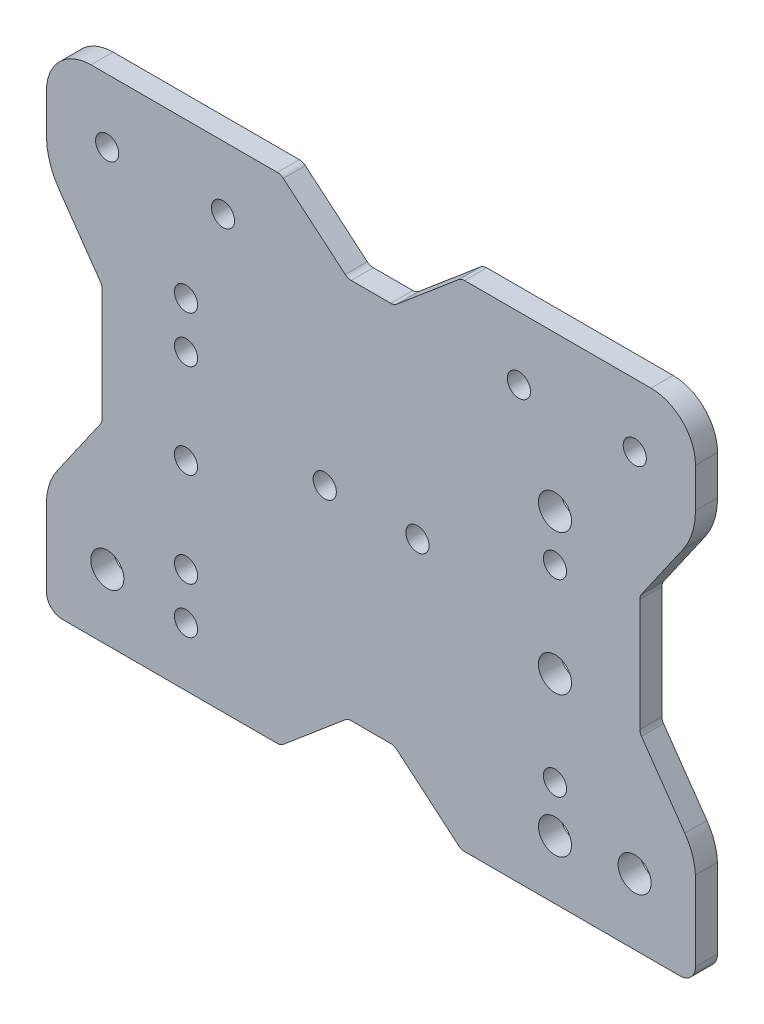
SolidWorks part; units mm, degrees
ref_plane "Front Plane" through (0, 0, 0) normal (0, 0, 1) x (1, 0, 0)
ref_plane "Top Plane" through (0, 0, 0) normal (0, 1, 0) x (1, 0, 0)
ref_plane "Right Plane" through (0, 0, 0) normal (1, 0, 0) x (0, 0, -1)
sketch "Sketch2" plane through (0, 0, 0) normal (0, 0, 1) x (1, 0, 0)
  line L0 (-0.0037, -60.8193) -> (-0.0037, -143.1004) construction
  line L1 (20.2046, -155.3178) -> (66.6535, -155.3178)
  line L2 (5.555, -143.572) -> (18.9147, -154.8463)
  line L3 (70.0163, -151.9551) -> (70.0095, -134.7792)
  line L4 (67.7231, -128.1324) -> (58.3686, -114.7091)
  line L5 (18.9147, -49.0734) -> (5.555, -60.3477)
  line L6 (60.4099, -48.6019) -> (20.2046, -48.6019)
  line L7 (70.0178, -66.6896) -> (70.018, -58.2099)
  line L8 (58.3765, -88.1311) -> (67.3098, -75.3119)
  line L9 (58.0094, -113.565) -> (58.0173, -89.274)
  line L1114 (-70.0237, -151.9551) -> (-70.0169, -134.7792)
  line L1126 (-67.7306, -128.1324) -> (-58.376, -114.7091)
  line L1127 (-58.0169, -113.565) -> (-58.0248, -89.274)
  line L1128 (-58.3839, -88.1311) -> (-67.3173, -75.3119)
  line L1140 (-70.0253, -66.6896) -> (-70.0254, -58.2099)
  line L1153 (-60.4174, -48.6019) -> (-20.2121, -48.6019)
  line L1154 (-18.9222, -49.0734) -> (-5.5625, -60.3477)
  line L1155 (-4.2726, -60.8193) -> (4.2651, -60.8193)
  line L1209 (4.2651, -143.1004) -> (-4.2726, -143.1004)
  line L1210 (-5.5625, -143.572) -> (-18.9222, -154.8463)
  line L1211 (-20.2121, -155.3178) -> (-66.6609, -155.3178)
  arc A0 (-70.0237, -151.9551) -> (-66.6609, -155.3178) centre (-66.6609, -151.9551) ccw
  arc A1 (-70.0169, -134.7792) -> (-67.7306, -128.1324) centre (-57.1992, -135.4716) cw
  arc A2 (-70.0254, -58.2099) -> (-60.4174, -48.6019) centre (-60.4174, -58.2099) cw
  arc A3 (-70.0253, -66.6896) -> (-67.3173, -75.3119) centre (-54.944, -66.6893) ccw
  arc A4 (70.0163, -151.9551) -> (66.6535, -155.3178) centre (66.6535, -151.9551) cw
  arc A5 (70.0095, -134.7792) -> (67.7231, -128.1324) centre (57.1918, -135.4716) ccw
  arc A6 (70.018, -58.2099) -> (60.4099, -48.6019) centre (60.4099, -58.2099) ccw
  arc A7 (70.0178, -66.6896) -> (67.3098, -75.3119) centre (54.9365, -66.6893) cw
  arc A8 (58.0094, -113.565) -> (58.3686, -114.7091) centre (60.0094, -113.5656) ccw
  arc A9 (58.0173, -89.274) -> (58.3765, -88.1311) centre (60.0173, -89.2746) cw
  arc A10 (18.9147, -154.8463) -> (20.2046, -155.3178) centre (20.2046, -153.3178) ccw
  arc A11 (4.2651, -143.1004) -> (5.555, -143.572) centre (4.2651, -145.1004) cw
  arc A12 (-5.5625, -143.572) -> (-4.2726, -143.1004) centre (-4.2726, -145.1004) cw
  arc A13 (-20.2121, -155.3178) -> (-18.9222, -154.8463) centre (-20.2121, -153.3178) ccw
  arc A14 (-58.0169, -113.565) -> (-58.376, -114.7091) centre (-60.0169, -113.5656) cw
  arc A15 (-58.0248, -89.274) -> (-58.3839, -88.1311) centre (-60.0248, -89.2746) ccw
  arc A16 (-5.5625, -60.3477) -> (-4.2726, -60.8193) centre (-4.2726, -58.8193) ccw
  arc A17 (5.555, -60.3477) -> (4.2651, -60.8193) centre (4.2651, -58.8193) cw
  arc A18 (18.9147, -49.0734) -> (20.2046, -48.6019) centre (20.2046, -50.6019) cw
  arc A19 (-20.2121, -48.6019) -> (-18.9222, -49.0734) centre (-20.2121, -50.6019) cw
  circle A28 centre (-56.9269, -62.2525) radius 2.5006
  circle A29 centre (-31.9269, -62.2525) radius 2.5006
  circle A30 centre (31.9194, -62.2525) radius 2.5006
  circle A31 centre (56.9194, -62.2525) radius 2.5006
  circle A32 centre (-39.9201, -81.9928) radius 2.5006
  circle A33 centre (-39.907, -91.9928) radius 2.5006
  circle A34 centre (-39.9201, -112.3174) radius 2.5006
  circle A35 centre (-39.907, -132.6328) radius 2.5006
  circle A36 centre (-39.9201, -142.6328) radius 2.5006
  circle A37 centre (10.0254, -101.9928) radius 2.5006
  circle A38 centre (-9.9746, -101.9928) radius 2.5006
  circle A39 centre (39.7004, -91.9928) radius 2.5006
  circle A40 centre (39.7004, -132.6328) radius 2.5006
  circle A41 centre (-56.8954, -141.1225) radius 3.5687
  circle A42 centre (39.7004, -142.6328) radius 3.5687
  circle A43 centre (39.7004, -112.3174) radius 3.5687
  circle A44 centre (39.7004, -81.9928) radius 3.5687
  circle A45 centre (56.8879, -141.1225) radius 3.5687
  point P24 (58.0092, -114.1935)
  point P27 (58.0175, -88.6462)
  point P30 (19.4735, -155.3178)
  point P33 (4.9963, -143.1004)
  point P37 (-5.0037, -143.1004)
  point P41 (-19.481, -155.3178)
  point P45 (-58.0167, -114.1935)
  point P49 (-58.025, -88.6462)
  point P53 (-5.0037, -60.8193)
  point P93 (4.9963, -60.8193)
  point P97 (19.4735, -48.6019)
  point P100 (-19.481, -48.6019)
  dimension "D1" = 2
sketch "Sketch3" plane through (0, 0, 0) normal (0, 0, 1) x (1, 0, 0)
  line L0 (109.789, 90.94) -> (109.3853, 90.4139)
  line L1 (109.3853, 90.4139) -> (109.1316, 89.8013)
  line L2 (109.1316, 89.8013) -> (109.045, 89.1439)
  line L3 (109.045, 89.1439) -> (109.045, 80.1439)
  line L4 (109.045, 80.1439) -> (109.1316, 79.4865)
  line L5 (109.1316, 79.4865) -> (109.3853, 78.8739)
  line L6 (109.3853, 78.8739) -> (109.789, 78.3479)
  line L7 (109.789, 78.3479) -> (110.315, 77.9442)
  line L8 (110.315, 77.9442) -> (110.9276, 77.6905)
  line L9 (110.9276, 77.6905) -> (111.585, 77.6039)
  line L10 (111.585, 77.6039) -> (112.2424, 77.6905)
  line L11 (112.2424, 77.6905) -> (112.855, 77.9442)
  line L12 (112.855, 77.9442) -> (113.3811, 78.3479)
  line L13 (113.3811, 78.3479) -> (113.7847, 78.8739)
  line L14 (113.7847, 78.8739) -> (114.0385, 79.4865)
  line L15 (114.0385, 79.4865) -> (114.125, 80.1439)
  line L16 (114.125, 80.1439) -> (114.125, 89.1439)
  line L17 (114.125, 89.1439) -> (114.0385, 89.8013)
  line L18 (114.0385, 89.8013) -> (113.7847, 90.4139)
  line L19 (113.7847, 90.4139) -> (113.3811, 90.94)
  line L20 (113.3811, 90.94) -> (112.855, 91.3436)
  line L21 (112.855, 91.3436) -> (112.2424, 91.5974)
  line L22 (112.2424, 91.5974) -> (111.585, 91.6839)
  line L23 (111.585, 91.6839) -> (110.9276, 91.5974)
  line L24 (110.9276, 91.5974) -> (110.315, 91.3436)
  line L25 (110.315, 91.3436) -> (109.789, 90.94)
  line L26 (-149.8395, -1.0925) -> (-148.8536, -1.1801)
  line L27 (-148.8536, -1.1801) -> (-147.9616, -1.4429)
  line L28 (-147.9616, -1.4429) -> (-147.1634, -1.8809)
  line L29 (-147.1634, -1.8809) -> (-146.4592, -2.4942)
  line L30 (-146.4592, -2.4942) -> (-145.8841, -3.2508)
  line L31 (-145.8841, -3.2508) -> (-145.4733, -4.119)
  line L32 (-145.4733, -4.119) -> (-145.2268, -5.0986)
  line L33 (-145.2268, -5.0986) -> (-145.1447, -6.1897)
  line L34 (-145.1447, -6.1897) -> (-145.2272, -7.2773)
  line L35 (-145.2272, -7.2773) -> (-145.475, -8.2529)
  line L36 (-145.475, -8.2529) -> (-145.8879, -9.1167)
  line L37 (-145.8879, -9.1167) -> (-146.4659, -9.8685)
  line L38 (-146.4659, -9.8685) -> (-147.1722, -10.4773)
  line L39 (-147.1722, -10.4773) -> (-147.9699, -10.9122)
  line L40 (-147.9699, -10.9122) -> (-148.859, -11.1732)
  line L41 (-148.859, -11.1732) -> (-149.8395, -11.2601)
  line L42 (-149.8395, -11.2601) -> (-150.8506, -11.17)
  line L43 (-150.8506, -11.17) -> (-151.7577, -10.8996)
  line L44 (-151.7577, -10.8996) -> (-152.5608, -10.449)
  line L45 (-152.5608, -10.449) -> (-153.26, -9.8182)
  line L46 (-153.26, -9.8182) -> (-153.8263, -9.0573)
  line L47 (-153.8263, -9.0573) -> (-154.2308, -8.2169)
  line L48 (-154.2308, -8.2169) -> (-154.4736, -7.2968)
  line L49 (-154.4736, -7.2968) -> (-154.5545, -6.297)
  line L50 (-154.5545, -6.297) -> (-154.4725, -5.1508)
  line L51 (-154.4725, -5.1508) -> (-154.2267, -4.1332)
  line L52 (-154.2267, -4.1332) -> (-153.8169, -3.2443)
  line L53 (-153.8169, -3.2443) -> (-153.2433, -2.4841)
  line L54 (-153.2433, -2.4841) -> (-152.5388, -1.8753)
  line L55 (-152.5388, -1.8753) -> (-151.7367, -1.4404)
  line L56 (-151.7367, -1.4404) -> (-150.8369, -1.1794)
  line L57 (-150.8369, -1.1794) -> (-149.8395, -1.0925)
  line L58 (-149.8529, -10.1468) -> (-149.1405, -10.0814)
  line L59 (-149.1405, -10.0814) -> (-148.499, -9.8852)
  line L60 (-148.499, -9.8852) -> (-147.9282, -9.5583)
  line L61 (-147.9282, -9.5583) -> (-147.4284, -9.1005)
  line L62 (-147.4284, -9.1005) -> (-147.0215, -8.5262)
  line L63 (-147.0215, -8.5262) -> (-146.73, -7.8497)
  line L64 (-146.73, -7.8497) -> (-146.5537, -7.0708)
  line L65 (-146.5537, -7.0708) -> (-146.4927, -6.1897)
  line L66 (-146.4927, -6.1897) -> (-146.5521, -5.286)
  line L67 (-146.5521, -5.286) -> (-146.73, -4.4929)
  line L68 (-146.73, -4.4929) -> (-147.0266, -3.8104)
  line L69 (-147.0266, -3.8104) -> (-147.4418, -3.2387)
  line L70 (-147.4418, -3.2387) -> (-147.9467, -2.7868)
  line L71 (-147.9467, -2.7868) -> (-148.5124, -2.464)
  line L72 (-148.5124, -2.464) -> (-149.1388, -2.2704)
  line L73 (-149.1388, -2.2704) -> (-149.8261, -2.2058)
  line L74 (-149.8261, -2.2058) -> (-150.5311, -2.2691)
  line L75 (-150.5311, -2.2691) -> (-151.1708, -2.459)
  line L76 (-151.1708, -2.459) -> (-151.7451, -2.7755)
  line L77 (-151.7451, -2.7755) -> (-152.254, -3.2186)
  line L78 (-152.254, -3.2186) -> (-152.6707, -3.7924)
  line L79 (-152.6707, -3.7924) -> (-152.9683, -4.5012)
  line L80 (-152.9683, -4.5012) -> (-153.1468, -5.3451)
  line L81 (-153.1468, -5.3451) -> (-153.2064, -6.3239)
  line L82 (-153.2064, -6.3239) -> (-153.1481, -7.1381)
  line L83 (-153.1481, -7.1381) -> (-152.9733, -7.8706)
  line L84 (-152.9733, -7.8706) -> (-152.682, -8.5214)
  line L85 (-152.682, -8.5214) -> (-152.2741, -9.0905)
  line L86 (-152.2741, -9.0905) -> (-151.7732, -9.5526)
  line L87 (-151.7732, -9.5526) -> (-151.2027, -9.8827)
  line L88 (-151.2027, -9.8827) -> (-150.5626, -10.0808)
  line L89 (-150.5626, -10.0808) -> (-149.8529, -10.1468)
  line L90 (-142.4552, -4.8953) -> (-142.0742, -4.4229)
  line L91 (-142.0742, -4.4229) -> (-141.6084, -4.0854)
  line L92 (-141.6084, -4.0854) -> (-141.0581, -3.883)
  line L93 (-141.0581, -3.883) -> (-140.423, -3.8155)
  line L94 (-140.423, -3.8155) -> (-139.759, -3.879)
  line L95 (-139.759, -3.879) -> (-139.1688, -4.0695)
  line L96 (-139.1688, -4.0695) -> (-138.6524, -4.387)
  line L97 (-138.6524, -4.387) -> (-138.2097, -4.8316)
  line L98 (-138.2097, -4.8316) -> (-137.8547, -5.378)
  line L99 (-137.8547, -5.378) -> (-137.6011, -6.0011)
  line L100 (-137.6011, -6.0011) -> (-137.4489, -6.7009)
  line L101 (-137.4489, -6.7009) -> (-137.3982, -7.4774)
  line L102 (-137.3982, -7.4774) -> (-137.4544, -8.3013)
  line L103 (-137.4544, -8.3013) -> (-137.6229, -9.036)
  line L104 (-137.6229, -9.036) -> (-137.9037, -9.6813)
  line L105 (-137.9037, -9.6813) -> (-138.2969, -10.2373)
  line L106 (-138.2969, -10.2373) -> (-138.7718, -10.6848)
  line L107 (-138.7718, -10.6848) -> (-139.2979, -11.0044)
  line L108 (-139.2979, -11.0044) -> (-139.8751, -11.1962)
  line L109 (-139.8751, -11.1962) -> (-140.5035, -11.2601)
  line L110 (-140.5035, -11.2601) -> (-141.0484, -11.2031)
  line L111 (-141.0484, -11.2031) -> (-141.5363, -11.0321)
  line L112 (-141.5363, -11.0321) -> (-141.9673, -10.7471)
  line L113 (-141.9673, -10.7471) -> (-142.3412, -10.348)
  line L114 (-142.3412, -10.348) -> (-142.3747, -10.348)
  line L115 (-142.3747, -10.348) -> (-142.3747, -13.8289)
  line L116 (-142.3747, -13.8289) -> (-143.582, -13.8289)
  line L117 (-143.582, -13.8289) -> (-143.582, -3.9764)
  line L118 (-143.582, -3.9764) -> (-142.482, -3.9764)
  line L119 (-142.482, -3.9764) -> (-142.482, -4.8953)
  line L120 (-142.482, -4.8953) -> (-142.4552, -4.8953)
  line L121 (-140.584, -10.2675) -> (-140.1797, -10.2237)
  line L122 (-140.1797, -10.2237) -> (-139.8118, -10.0923)
  line L123 (-139.8118, -10.0923) -> (-139.4805, -9.8733)
  line L124 (-139.4805, -9.8733) -> (-139.1856, -9.5666)
  line L125 (-139.1856, -9.5666) -> (-138.9435, -9.1732)
  line L126 (-138.9435, -9.1732) -> (-138.7706, -8.6939)
  line L127 (-138.7706, -8.6939) -> (-138.6668, -8.1286)
  line L128 (-138.6668, -8.1286) -> (-138.6323, -7.4774)
  line L129 (-138.6323, -7.4774) -> (-138.7656, -6.3205)
  line L130 (-138.7656, -6.3205) -> (-138.9322, -5.8552)
  line L131 (-138.9322, -5.8552) -> (-139.1655, -5.4654)
  line L132 (-139.1655, -5.4654) -> (-139.4507, -5.1573)
  line L133 (-139.4507, -5.1573) -> (-139.7733, -4.9372)
  line L134 (-139.7733, -4.9372) -> (-140.1331, -4.8052)
  line L135 (-140.1331, -4.8052) -> (-140.5303, -4.7611)
  line L136 (-140.5303, -4.7611) -> (-140.9405, -4.8102)
  line L137 (-140.9405, -4.8102) -> (-141.3125, -4.9573)
  line L138 (-141.3125, -4.9573) -> (-141.6464, -5.2025)
  line L139 (-141.6464, -5.2025) -> (-141.9421, -5.5459)
  line L140 (-141.9421, -5.5459) -> (-142.1842, -5.9671)
  line L141 (-142.1842, -5.9671) -> (-142.3571, -6.4463)
  line L142 (-142.3571, -6.4463) -> (-142.4609, -6.9832)
  line L143 (-142.4609, -6.9832) -> (-142.4954, -7.578)
  line L144 (-142.4954, -7.578) -> (-142.363, -8.74)
  line L145 (-142.363, -8.74) -> (-142.1974, -9.2015)
  line L146 (-142.1974, -9.2015) -> (-141.9656, -9.5834)
  line L147 (-141.9656, -9.5834) -> (-141.6805, -9.8827)
  line L148 (-141.6805, -9.8827) -> (-141.3553, -10.0965)
  line L149 (-141.3553, -10.0965) -> (-140.9897, -10.2248)
  line L150 (-140.9897, -10.2248) -> (-140.584, -10.2675)
  line L151 (-133.1795, -11.0791) -> (-134.085, -11.1864)
  line L152 (-134.085, -11.1864) -> (-134.7691, -11.1168)
  line L153 (-134.7691, -11.1168) -> (-135.2386, -10.908)
  line L154 (-135.2386, -10.908) -> (-135.5303, -10.592)
  line L155 (-135.5303, -10.592) -> (-135.6812, -10.2004)
  line L156 (-135.6812, -10.2004) -> (-135.7617, -9.0066)
  line L157 (-135.7617, -9.0066) -> (-135.7617, -4.9087)
  line L158 (-135.7617, -4.9087) -> (-136.6403, -4.9087)
  line L159 (-136.6403, -4.9087) -> (-136.6403, -3.9764)
  line L160 (-136.6403, -3.9764) -> (-135.7617, -3.9764)
  line L161 (-135.7617, -3.9764) -> (-135.7617, -2.2058)
  line L162 (-135.7617, -2.2058) -> (-134.5545, -1.4748)
  line L163 (-134.5545, -1.4748) -> (-134.5545, -3.9764)
  line L164 (-134.5545, -3.9764) -> (-133.3472, -3.9764)
  line L165 (-133.3472, -3.9764) -> (-133.3472, -4.9087)
  line L166 (-133.3472, -4.9087) -> (-134.5545, -4.9087)
  line L167 (-134.5545, -4.9087) -> (-134.5545, -9.0737)
  line L168 (-134.5545, -9.0737) -> (-134.5268, -9.5323)
  line L169 (-134.5268, -9.5323) -> (-134.4438, -9.8349)
  line L170 (-134.4438, -9.8349) -> (-134.2485, -10.0034)
  line L171 (-134.2485, -10.0034) -> (-133.8838, -10.0596)
  line L172 (-133.8838, -10.0596) -> (-133.3472, -10.0059)
  line L173 (-133.3472, -10.0059) -> (-133.1795, -11.0791)
  line L174 (-130.9327, -11.0925) -> (-132.14, -11.0925)
  line L175 (-132.14, -11.0925) -> (-132.14, -3.9764)
  line L176 (-132.14, -3.9764) -> (-130.9327, -3.9764)
  line L177 (-130.9327, -3.9764) -> (-130.9327, -11.0925)
  line L178 (-130.9327, -2.6283) -> (-132.14, -2.6283)
  line L179 (-132.14, -2.6283) -> (-132.14, -1.2601)
  line L180 (-132.14, -1.2601) -> (-130.9327, -1.2601)
  line L181 (-130.9327, -1.2601) -> (-130.9327, -2.6283)
  line L182 (-126.1909, -3.8155) -> (-125.5008, -3.8742)
  line L183 (-125.5008, -3.8742) -> (-124.8722, -4.0502)
  line L184 (-124.8722, -4.0502) -> (-124.3052, -4.3436)
  line L185 (-124.3052, -4.3436) -> (-123.7999, -4.7544)
  line L186 (-123.7999, -4.7544) -> (-123.3847, -5.2734)
  line L187 (-123.3847, -5.2734) -> (-123.0882, -5.8913)
  line L188 (-123.0882, -5.8913) -> (-122.9102, -6.6081)
  line L189 (-122.9102, -6.6081) -> (-122.8509, -7.4238)
  line L190 (-122.8509, -7.4238) -> (-122.915, -8.3965)
  line L191 (-122.915, -8.3965) -> (-123.1074, -9.2154)
  line L192 (-123.1074, -9.2154) -> (-123.4281, -9.8804)
  line L193 (-123.4281, -9.8804) -> (-123.8771, -10.3916)
  line L194 (-123.8771, -10.3916) -> (-124.4065, -10.7716)
  line L195 (-124.4065, -10.7716) -> (-124.9686, -11.043)
  line L196 (-124.9686, -11.043) -> (-125.5634, -11.2059)
  line L197 (-125.5634, -11.2059) -> (-126.1909, -11.2601)
  line L198 (-126.1909, -11.2601) -> (-126.8428, -11.2044)
  line L199 (-126.8428, -11.2044) -> (-127.4502, -11.0371)
  line L200 (-127.4502, -11.0371) -> (-128.0131, -10.7584)
  line L201 (-128.0131, -10.7584) -> (-128.5316, -10.3681)
  line L202 (-128.5316, -10.3681) -> (-128.9659, -9.8567)
  line L203 (-128.9659, -9.8567) -> (-129.2761, -9.2145)
  line L204 (-129.2761, -9.2145) -> (-129.4622, -8.4416)
  line L205 (-129.4622, -8.4416) -> (-129.5243, -7.5378)
  line L206 (-129.5243, -7.5378) -> (-129.4643, -6.6586)
  line L207 (-129.4643, -6.6586) -> (-129.2845, -5.8988)
  line L208 (-129.2845, -5.8988) -> (-128.9848, -5.2585)
  line L209 (-128.9848, -5.2585) -> (-128.5652, -4.7377)
  line L210 (-128.5652, -4.7377) -> (-128.0571, -4.3342)
  line L211 (-128.0571, -4.3342) -> (-127.4921, -4.046)
  line L212 (-127.4921, -4.046) -> (-126.87, -3.8731)
  line L213 (-126.87, -3.8731) -> (-126.1909, -3.8155)
  line L214 (-126.1909, -10.2675) -> (-125.7055, -10.2197)
  line L215 (-125.7055, -10.2197) -> (-125.2822, -10.0764)
  line L216 (-125.2822, -10.0764) -> (-124.9208, -9.8374)
  line L217 (-124.9208, -9.8374) -> (-124.6215, -9.5029)
  line L218 (-124.6215, -9.5029) -> (-124.3868, -9.0905)
  line L219 (-124.3868, -9.0905) -> (-124.2191, -8.6176)
  line L220 (-124.2191, -8.6176) -> (-124.085, -7.4909)
  line L221 (-124.085, -7.4909) -> (-124.1229, -6.8646)
  line L222 (-124.1229, -6.8646) -> (-124.2367, -6.3205)
  line L223 (-124.2367, -6.3205) -> (-124.4264, -5.8586)
  line L224 (-124.4264, -5.8586) -> (-124.6919, -5.4788)
  line L225 (-124.6919, -5.4788) -> (-125.0132, -5.1824)
  line L226 (-125.0132, -5.1824) -> (-125.3702, -4.9707)
  line L227 (-125.3702, -4.9707) -> (-125.7627, -4.8437)
  line L228 (-125.7627, -4.8437) -> (-126.1909, -4.8014)
  line L229 (-126.1909, -4.8014) -> (-126.6298, -4.8444)
  line L230 (-126.6298, -4.8444) -> (-127.0276, -4.9732)
  line L231 (-127.0276, -4.9732) -> (-127.3843, -5.1881)
  line L232 (-127.3843, -5.1881) -> (-127.7, -5.4888)
  line L233 (-127.7, -5.4888) -> (-127.9582, -5.8747)
  line L234 (-127.9582, -5.8747) -> (-128.1426, -6.3448)
  line L235 (-128.1426, -6.3448) -> (-128.2533, -6.8992)
  line L236 (-128.2533, -6.8992) -> (-128.2902, -7.5378)
  line L237 (-128.2902, -7.5378) -> (-128.2527, -8.1735)
  line L238 (-128.2527, -8.1735) -> (-128.1401, -8.7258)
  line L239 (-128.1401, -8.7258) -> (-127.9526, -9.1946)
  line L240 (-127.9526, -9.1946) -> (-127.6899, -9.5801)
  line L241 (-127.6899, -9.5801) -> (-127.3711, -9.8808)
  line L242 (-127.3711, -9.8808) -> (-127.0151, -10.0956)
  line L243 (-127.0151, -10.0956) -> (-126.6216, -10.2245)
  line L244 (-126.6216, -10.2245) -> (-126.1909, -10.2675)
  line L245 (-115.6343, -11.0925) -> (-116.8482, -11.0925)
  line L246 (-116.8482, -11.0925) -> (-116.8482, -6.7665)
  line L247 (-116.8482, -6.7665) -> (-116.9463, -5.8443)
  line L248 (-116.9463, -5.8443) -> (-117.0689, -5.5115)
  line L249 (-117.0689, -5.5115) -> (-117.2406, -5.2642)
  line L250 (-117.2406, -5.2642) -> (-117.7092, -4.9573)
  line L251 (-117.7092, -4.9573) -> (-118.3304, -4.855)
  line L252 (-118.3304, -4.855) -> (-118.8527, -4.9204)
  line L253 (-118.8527, -4.9204) -> (-119.3465, -5.1166)
  line L254 (-119.3465, -5.1166) -> (-119.7565, -5.4318)
  line L255 (-119.7565, -5.4318) -> (-120.0273, -5.8544)
  line L256 (-120.0273, -5.8544) -> (-120.1782, -6.4295)
  line L257 (-120.1782, -6.4295) -> (-120.2285, -7.2025)
  line L258 (-120.2285, -7.2025) -> (-120.2285, -11.0925)
  line L259 (-120.2285, -11.0925) -> (-121.4357, -11.0925)
  line L260 (-121.4357, -11.0925) -> (-121.4357, -3.9764)
  line L261 (-121.4357, -3.9764) -> (-120.3492, -3.9764)
  line L262 (-120.3492, -3.9764) -> (-120.3492, -4.9825)
  line L263 (-120.3492, -4.9825) -> (-120.3224, -4.9825)
  line L264 (-120.3224, -4.9825) -> (-119.8957, -4.4719)
  line L265 (-119.8957, -4.4719) -> (-119.3801, -4.1072)
  line L266 (-119.3801, -4.1072) -> (-118.7756, -3.8884)
  line L267 (-118.7756, -3.8884) -> (-118.0823, -3.8155)
  line L268 (-118.0823, -3.8155) -> (-117.5223, -3.8658)
  line L269 (-117.5223, -3.8658) -> (-116.9689, -4.0167)
  line L270 (-116.9689, -4.0167) -> (-116.4785, -4.2682)
  line L271 (-116.4785, -4.2682) -> (-116.1071, -4.6203)
  line L272 (-116.1071, -4.6203) -> (-115.8531, -5.0361)
  line L273 (-115.8531, -5.0361) -> (-115.7147, -5.4788)
  line L274 (-115.7147, -5.4788) -> (-115.6343, -6.7129)
  line L275 (-115.6343, -6.7129) -> (-115.6343, -11.0925)
  line L276 (-107.6396, -11.0925) -> (-108.9072, -11.0925)
  line L277 (-108.9072, -11.0925) -> (-109.0565, -10.7051)
  line L278 (-109.0565, -10.7051) -> (-109.1554, -10.2139)
  line L279 (-109.1554, -10.2139) -> (-109.7745, -10.6716)
  line L280 (-109.7745, -10.6716) -> (-110.418, -10.9986)
  line L281 (-110.418, -10.9986) -> (-111.0857, -11.1947)
  line L282 (-111.0857, -11.1947) -> (-111.7778, -11.2601)
  line L283 (-111.7778, -11.2601) -> (-112.3114, -11.2249)
  line L284 (-112.3114, -11.2249) -> (-112.7855, -11.1193)
  line L285 (-112.7855, -11.1193) -> (-113.2001, -10.9432)
  line L286 (-113.2001, -10.9432) -> (-113.5551, -10.6968)
  line L287 (-113.5551, -10.6968) -> (-113.8397, -10.3924)
  line L288 (-113.8397, -10.3924) -> (-114.0431, -10.0428)
  line L289 (-114.0431, -10.0428) -> (-114.165, -9.648)
  line L290 (-114.165, -9.648) -> (-114.2057, -9.2078)
  line L291 (-114.2057, -9.2078) -> (-114.1665, -8.7847)
  line L292 (-114.1665, -8.7847) -> (-114.0489, -8.4005)
  line L293 (-114.0489, -8.4005) -> (-113.853, -8.0553)
  line L294 (-113.853, -8.0553) -> (-113.5786, -7.7491)
  line L295 (-113.5786, -7.7491) -> (-113.2074, -7.4865)
  line L296 (-113.2074, -7.4865) -> (-112.721, -7.272)
  line L297 (-112.721, -7.272) -> (-111.4022, -6.9878)
  line L298 (-111.4022, -6.9878) -> (-110.2754, -6.8202)
  line L299 (-110.2754, -6.8202) -> (-109.2359, -6.572)
  line L300 (-109.2359, -6.572) -> (-109.2694, -5.8041)
  line L301 (-109.2694, -5.8041) -> (-109.4673, -5.3379)
  line L302 (-109.4673, -5.3379) -> (-109.681, -5.12)
  line L303 (-109.681, -5.12) -> (-109.9938, -4.9489)
  line L304 (-109.9938, -4.9489) -> (-110.418, -4.8383)
  line L305 (-110.418, -4.8383) -> (-110.9663, -4.8014)
  line L306 (-110.9663, -4.8014) -> (-111.6629, -4.8735)
  line L307 (-111.6629, -4.8735) -> (-112.197, -5.0898)
  line L308 (-112.197, -5.0898) -> (-112.5784, -5.5023)
  line L309 (-112.5784, -5.5023) -> (-112.8174, -6.1629)
  line L310 (-112.8174, -6.1629) -> (-113.9978, -6.0086)
  line L311 (-113.9978, -6.0086) -> (-113.8624, -5.496)
  line L312 (-113.8624, -5.496) -> (-113.6507, -5.0512)
  line L313 (-113.6507, -5.0512) -> (-113.3627, -4.6744)
  line L314 (-113.3627, -4.6744) -> (-112.9985, -4.3654)
  line L315 (-112.9985, -4.3654) -> (-112.5583, -4.1248)
  line L316 (-112.5583, -4.1248) -> (-112.0427, -3.953)
  line L317 (-112.0427, -3.953) -> (-111.4517, -3.8498)
  line L318 (-111.4517, -3.8498) -> (-110.7852, -3.8155)
  line L319 (-110.7852, -3.8155) -> (-109.6743, -3.9102)
  line L320 (-109.6743, -3.9102) -> (-108.9039, -4.1944)
  line L321 (-108.9039, -4.1944) -> (-108.4193, -4.6128)
  line L322 (-108.4193, -4.6128) -> (-108.1661, -5.1099)
  line L323 (-108.1661, -5.1099) -> (-108.063, -5.7236)
  line L324 (-108.063, -5.7236) -> (-108.0286, -6.4915)
  line L325 (-108.0286, -6.4915) -> (-108.0286, -8.1146)
  line L326 (-108.0286, -8.1146) -> (-107.9716, -10.1032)
  line L327 (-107.9716, -10.1032) -> (-107.8601, -10.6037)
  line L328 (-107.8601, -10.6037) -> (-107.6396, -11.0925)
  line L329 (-109.2359, -7.9603) -> (-109.2359, -7.5244)
  line L330 (-109.2359, -7.5244) -> (-110.2872, -7.8069)
  line L331 (-110.2872, -7.8069) -> (-111.5498, -8.0241)
  line L332 (-111.5498, -8.0241) -> (-112.1484, -8.1655)
  line L333 (-112.1484, -8.1655) -> (-112.5759, -8.4055)
  line L334 (-112.5759, -8.4055) -> (-112.8325, -8.744)
  line L335 (-112.8325, -8.744) -> (-112.918, -9.181)
  line L336 (-112.918, -9.181) -> (-112.8257, -9.6278)
  line L337 (-112.8257, -9.6278) -> (-112.5491, -9.9892)
  line L338 (-112.5491, -9.9892) -> (-112.0997, -10.2281)
  line L339 (-112.0997, -10.2281) -> (-111.4894, -10.3078)
  line L340 (-111.4894, -10.3078) -> (-110.6502, -10.1745)
  line L341 (-110.6502, -10.1745) -> (-109.9166, -9.7746)
  line L342 (-109.9166, -9.7746) -> (-109.6188, -9.4612)
  line L343 (-109.6188, -9.4612) -> (-109.4061, -9.0544)
  line L344 (-109.4061, -9.0544) -> (-109.2784, -8.5541)
  line L345 (-109.2784, -8.5541) -> (-109.2359, -7.9603)
  line L346 (-104.9636, -11.0925) -> (-106.1708, -11.0925)
  line L347 (-106.1708, -11.0925) -> (-106.1708, -1.2601)
  line L348 (-106.1708, -1.2601) -> (-104.9636, -1.2601)
  line L349 (-104.9636, -1.2601) -> (-104.9636, -11.0925)
  line L350 (-92.1333, -2.4271) -> (-95.3861, -2.4271)
  line L351 (-95.3861, -2.4271) -> (-95.3861, -11.0925)
  line L352 (-95.3861, -11.0925) -> (-96.694, -11.0925)
  line L353 (-96.694, -11.0925) -> (-96.694, -2.4271)
  line L354 (-96.694, -2.4271) -> (-99.92, -2.4271)
  line L355 (-99.92, -2.4271) -> (-99.92, -1.2601)
  line L356 (-99.92, -1.2601) -> (-92.1333, -1.2601)
  line L357 (-92.1333, -1.2601) -> (-92.1333, -2.4271)
  line L358 (-84.7422, -11.0925) -> (-86.0099, -11.0925)
  line L359 (-86.0099, -11.0925) -> (-86.1591, -10.7051)
  line L360 (-86.1591, -10.7051) -> (-86.258, -10.2139)
  line L361 (-86.258, -10.2139) -> (-86.8771, -10.6716)
  line L362 (-86.8771, -10.6716) -> (-87.5206, -10.9986)
  line L363 (-87.5206, -10.9986) -> (-88.1883, -11.1947)
  line L364 (-88.1883, -11.1947) -> (-88.8804, -11.2601)
  line L365 (-88.8804, -11.2601) -> (-89.414, -11.2249)
  line L366 (-89.414, -11.2249) -> (-89.8881, -11.1193)
  line L367 (-89.8881, -11.1193) -> (-90.3027, -10.9432)
  line L368 (-90.3027, -10.9432) -> (-90.6577, -10.6968)
  line L369 (-90.6577, -10.6968) -> (-90.9424, -10.3924)
  line L370 (-90.9424, -10.3924) -> (-91.1457, -10.0428)
  line L371 (-91.1457, -10.0428) -> (-91.2676, -9.648)
  line L372 (-91.2676, -9.648) -> (-91.3083, -9.2078)
  line L373 (-91.3083, -9.2078) -> (-91.2691, -8.7847)
  line L374 (-91.2691, -8.7847) -> (-91.1515, -8.4005)
  line L375 (-91.1515, -8.4005) -> (-90.9556, -8.0553)
  line L376 (-90.9556, -8.0553) -> (-90.6812, -7.7491)
  line L377 (-90.6812, -7.7491) -> (-90.31, -7.4865)
  line L378 (-90.31, -7.4865) -> (-89.8236, -7.272)
  line L379 (-89.8236, -7.272) -> (-88.5048, -6.9878)
  line L380 (-88.5048, -6.9878) -> (-87.3781, -6.8202)
  line L381 (-87.3781, -6.8202) -> (-86.3385, -6.572)
  line L382 (-86.3385, -6.572) -> (-86.372, -5.8041)
  line L383 (-86.372, -5.8041) -> (-86.5699, -5.3379)
  line L384 (-86.5699, -5.3379) -> (-86.7837, -5.12)
  line L385 (-86.7837, -5.12) -> (-87.0964, -4.9489)
  line L386 (-87.0964, -4.9489) -> (-87.5206, -4.8383)
  line L387 (-87.5206, -4.8383) -> (-88.0689, -4.8014)
  line L388 (-88.0689, -4.8014) -> (-88.7656, -4.8735)
  line L389 (-88.7656, -4.8735) -> (-89.2996, -5.0898)
  line L390 (-89.2996, -5.0898) -> (-89.681, -5.5023)
  line L391 (-89.681, -5.5023) -> (-89.92, -6.1629)
  line L392 (-89.92, -6.1629) -> (-91.1004, -6.0086)
  line L393 (-91.1004, -6.0086) -> (-90.965, -5.496)
  line L394 (-90.965, -5.496) -> (-90.7533, -5.0512)
  line L395 (-90.7533, -5.0512) -> (-90.4653, -4.6744)
  line L396 (-90.4653, -4.6744) -> (-90.1011, -4.3654)
  line L397 (-90.1011, -4.3654) -> (-89.6609, -4.1248)
  line L398 (-89.6609, -4.1248) -> (-89.1453, -3.953)
  line L399 (-89.1453, -3.953) -> (-88.5543, -3.8498)
  line L400 (-88.5543, -3.8498) -> (-87.8878, -3.8155)
  line L401 (-87.8878, -3.8155) -> (-86.777, -3.9102)
  line L402 (-86.777, -3.9102) -> (-86.0065, -4.1944)
  line L403 (-86.0065, -4.1944) -> (-85.5219, -4.6128)
  line L404 (-85.5219, -4.6128) -> (-85.2687, -5.1099)
  line L405 (-85.2687, -5.1099) -> (-85.1656, -5.7236)
  line L406 (-85.1656, -5.7236) -> (-85.1312, -6.4915)
  line L407 (-85.1312, -6.4915) -> (-85.1312, -8.1146)
  line L408 (-85.1312, -8.1146) -> (-85.0742, -10.1032)
  line L409 (-85.0742, -10.1032) -> (-84.9627, -10.6037)
  line L410 (-84.9627, -10.6037) -> (-84.7422, -11.0925)
  line L411 (-86.3385, -7.9603) -> (-86.3385, -7.5244)
  line L412 (-86.3385, -7.5244) -> (-87.3898, -7.8069)
  line L413 (-87.3898, -7.8069) -> (-88.6524, -8.0241)
  line L414 (-88.6524, -8.0241) -> (-89.251, -8.1655)
  line L415 (-89.251, -8.1655) -> (-89.6785, -8.4055)
  line L416 (-89.6785, -8.4055) -> (-89.9351, -8.744)
  line L417 (-89.9351, -8.744) -> (-90.0206, -9.181)
  line L418 (-90.0206, -9.181) -> (-89.9284, -9.6278)
  line L419 (-89.9284, -9.6278) -> (-89.6517, -9.9892)
  line L420 (-89.6517, -9.9892) -> (-89.2023, -10.2281)
  line L421 (-89.2023, -10.2281) -> (-88.592, -10.3078)
  line L422 (-88.592, -10.3078) -> (-87.7528, -10.1745)
  line L423 (-87.7528, -10.1745) -> (-87.0192, -9.7746)
  line L424 (-87.0192, -9.7746) -> (-86.7214, -9.4612)
  line L425 (-86.7214, -9.4612) -> (-86.5087, -9.0544)
  line L426 (-86.5087, -9.0544) -> (-86.381, -8.5541)
  line L427 (-86.381, -8.5541) -> (-86.3385, -7.9603)
  line L428 (-82.0662, -11.0925) -> (-83.2734, -11.0925)
  line L429 (-83.2734, -11.0925) -> (-83.2734, -1.2601)
  line L430 (-83.2734, -1.2601) -> (-82.0662, -1.2601)
  line L431 (-82.0662, -1.2601) -> (-82.0662, -11.0925)
  line L432 (-79.0145, -11.0925) -> (-80.2218, -11.0925)
  line L433 (-80.2218, -11.0925) -> (-80.2218, -1.2601)
  line L434 (-80.2218, -1.2601) -> (-79.0145, -1.2601)
  line L435 (-79.0145, -1.2601) -> (-79.0145, -11.0925)
  line L436 (-70.9864, -7.8396) -> (-76.3184, -7.8396)
  line L437 (-76.3184, -7.8396) -> (-76.2486, -8.395)
  line L438 (-76.2486, -8.395) -> (-76.113, -8.8809)
  line L439 (-76.113, -8.8809) -> (-75.9116, -9.2971)
  line L440 (-75.9116, -9.2971) -> (-75.6443, -9.6438)
  line L441 (-75.6443, -9.6438) -> (-75.3255, -9.9167)
  line L442 (-75.3255, -9.9167) -> (-74.9694, -10.1116)
  line L443 (-74.9694, -10.1116) -> (-74.576, -10.2285)
  line L444 (-74.576, -10.2285) -> (-74.1453, -10.2675)
  line L445 (-74.1453, -10.2675) -> (-73.5099, -10.1761)
  line L446 (-73.5099, -10.1761) -> (-72.985, -9.902)
  line L447 (-72.985, -9.902) -> (-72.5709, -9.4434)
  line L448 (-72.5709, -9.4434) -> (-72.2674, -8.7987)
  line L449 (-72.2674, -8.7987) -> (-71.0266, -8.953)
  line L450 (-71.0266, -8.953) -> (-71.209, -9.4774)
  line L451 (-71.209, -9.4774) -> (-71.4542, -9.9372)
  line L452 (-71.4542, -9.9372) -> (-71.7623, -10.3325)
  line L453 (-71.7623, -10.3325) -> (-72.1333, -10.6632)
  line L454 (-72.1333, -10.6632) -> (-72.5608, -10.9244)
  line L455 (-72.5608, -10.9244) -> (-73.0387, -11.1109)
  line L456 (-73.0387, -11.1109) -> (-73.5669, -11.2228)
  line L457 (-73.5669, -11.2228) -> (-74.1453, -11.2601)
  line L458 (-74.1453, -11.2601) -> (-74.903, -11.1987)
  line L459 (-74.903, -11.1987) -> (-75.5731, -11.0145)
  line L460 (-75.5731, -11.0145) -> (-76.1555, -10.7074)
  line L461 (-76.1555, -10.7074) -> (-76.6504, -10.2776)
  line L462 (-76.6504, -10.2776) -> (-77.045, -9.7412)
  line L463 (-77.045, -9.7412) -> (-77.3269, -9.1148)
  line L464 (-77.3269, -9.1148) -> (-77.4961, -8.3982)
  line L465 (-77.4961, -8.3982) -> (-77.5524, -7.5915)
  line L466 (-77.5524, -7.5915) -> (-77.4977, -6.7896)
  line L467 (-77.4977, -6.7896) -> (-77.3336, -6.0673)
  line L468 (-77.3336, -6.0673) -> (-77.0601, -5.4247)
  line L469 (-77.0601, -5.4247) -> (-76.6772, -4.8617)
  line L470 (-76.6772, -4.8617) -> (-76.1949, -4.404)
  line L471 (-76.1949, -4.404) -> (-75.6234, -4.077)
  line L472 (-75.6234, -4.077) -> (-74.9625, -3.8809)
  line L473 (-74.9625, -3.8809) -> (-74.2124, -3.8155)
  line L474 (-74.2124, -3.8155) -> (-73.4487, -3.901)
  line L475 (-73.4487, -3.901) -> (-72.7134, -4.1575)
  line L476 (-72.7134, -4.1575) -> (-72.0469, -4.6195)
  line L477 (-72.0469, -4.6195) -> (-71.4894, -5.3212)
  line L478 (-71.4894, -5.3212) -> (-71.2693, -5.7867)
  line L479 (-71.2693, -5.7867) -> (-71.1121, -6.3616)
  line L480 (-71.1121, -6.3616) -> (-70.9864, -7.8396)
  line L481 (-72.2272, -6.847) -> (-72.297, -6.3417)
  line L482 (-72.297, -6.3417) -> (-72.4326, -5.9122)
  line L483 (-72.4326, -5.9122) -> (-72.634, -5.5586)
  line L484 (-72.634, -5.5586) -> (-72.9012, -5.2809)
  line L485 (-72.9012, -5.2809) -> (-73.5291, -4.9213)
  line L486 (-73.5291, -4.9213) -> (-74.2124, -4.8014)
  line L487 (-74.2124, -4.8014) -> (-74.6194, -4.837)
  line L488 (-74.6194, -4.837) -> (-74.9887, -4.9439)
  line L489 (-74.9887, -4.9439) -> (-75.3203, -5.1221)
  line L490 (-75.3203, -5.1221) -> (-75.6141, -5.3715)
  line L491 (-75.6141, -5.3715) -> (-76.0484, -6.0254)
  line L492 (-76.0484, -6.0254) -> (-76.2513, -6.847)
  line L493 (-76.2513, -6.847) -> (-72.2272, -6.847)
  line L494 (-65.6946, -4.1978) -> (-66.1105, -5.3111)
  line L495 (-66.1105, -5.3111) -> (-66.5548, -5.1149)
  line L496 (-66.5548, -5.1149) -> (-66.9891, -5.0495)
  line L497 (-66.9891, -5.0495) -> (-67.3072, -5.0875)
  line L498 (-67.3072, -5.0875) -> (-67.5843, -5.2013)
  line L499 (-67.5843, -5.2013) -> (-67.8203, -5.391)
  line L500 (-67.8203, -5.391) -> (-68.0152, -5.6565)
  line L501 (-68.0152, -5.6565) -> (-68.2768, -6.3851)
  line L502 (-68.2768, -6.3851) -> (-68.364, -7.3567)
  line L503 (-68.364, -7.3567) -> (-68.364, -11.0925)
  line L504 (-68.364, -11.0925) -> (-69.5712, -11.0925)
  line L505 (-69.5712, -11.0925) -> (-69.5712, -3.9764)
  line L506 (-69.5712, -3.9764) -> (-68.4713, -3.9764)
  line L507 (-68.4713, -3.9764) -> (-68.4713, -5.0495)
  line L508 (-68.4713, -5.0495) -> (-68.4445, -5.0495)
  line L509 (-68.4445, -5.0495) -> (-68.1338, -4.5096)
  line L510 (-68.1338, -4.5096) -> (-67.7788, -4.124)
  line L511 (-67.7788, -4.124) -> (-67.3793, -3.8926)
  line L512 (-67.3793, -3.8926) -> (-66.9354, -3.8155)
  line L513 (-66.9354, -3.8155) -> (-66.3167, -3.911)
  line L514 (-66.3167, -3.911) -> (-65.6946, -4.1978)
  line L515 (-54.038, -11.0925) -> (-61.8113, -11.0925)
  line L516 (-61.8113, -11.0925) -> (-61.8113, -9.8718)
  line L517 (-61.8113, -9.8718) -> (-56.7744, -3.5941)
  line L518 (-56.7744, -3.5941) -> (-56.419, -3.1548)
  line L519 (-56.419, -3.1548) -> (-55.755, -2.4271)
  line L520 (-55.755, -2.4271) -> (-61.2479, -2.4271)
  line L521 (-61.2479, -2.4271) -> (-61.2479, -1.2601)
  line L522 (-61.2479, -1.2601) -> (-54.2057, -1.2601)
  line L523 (-54.2057, -1.2601) -> (-54.2057, -2.4271)
  line L524 (-54.2057, -2.4271) -> (-59.7255, -9.2212)
  line L525 (-59.7255, -9.2212) -> (-60.3157, -9.9255)
  line L526 (-60.3157, -9.9255) -> (-54.038, -9.9255)
  line L527 (-54.038, -9.9255) -> (-54.038, -11.0925)
  line L528 (-48.7932, -1.2601) -> (-45.0843, -1.2601)
  line L529 (-45.0843, -1.2601) -> (-43.5719, -1.3473)
  line L530 (-43.5719, -1.3473) -> (-42.9607, -1.5041)
  line L531 (-42.9607, -1.5041) -> (-42.3948, -1.8)
  line L532 (-42.3948, -1.8) -> (-41.9178, -2.231)
  line L533 (-41.9178, -2.231) -> (-41.5732, -2.7927)
  line L534 (-41.5732, -2.7927) -> (-41.3645, -3.434)
  line L535 (-41.3645, -3.434) -> (-41.2949, -4.1039)
  line L536 (-41.2949, -4.1039) -> (-41.3496, -4.7509)
  line L537 (-41.3496, -4.7509) -> (-41.5137, -5.3304)
  line L538 (-41.5137, -5.3304) -> (-41.7872, -5.8424)
  line L539 (-41.7872, -5.8424) -> (-42.1701, -6.287)
  line L540 (-42.1701, -6.287) -> (-42.6738, -6.6464)
  line L541 (-42.6738, -6.6464) -> (-43.3095, -6.9032)
  line L542 (-43.3095, -6.9032) -> (-44.0772, -7.0572)
  line L543 (-44.0772, -7.0572) -> (-44.977, -7.1086)
  line L544 (-44.977, -7.1086) -> (-47.4921, -7.1086)
  line L545 (-47.4921, -7.1086) -> (-47.4921, -11.0925)
  line L546 (-47.4921, -11.0925) -> (-48.7932, -11.0925)
  line L547 (-48.7932, -11.0925) -> (-48.7932, -1.2601)
  line L548 (-47.4921, -5.9416) -> (-44.9636, -5.9416)
  line L549 (-44.9636, -5.9416) -> (-43.9483, -5.8292)
  line L550 (-43.9483, -5.8292) -> (-43.5495, -5.6888)
  line L551 (-43.5495, -5.6888) -> (-43.2231, -5.4922)
  line L552 (-43.2231, -5.4922) -> (-42.9693, -5.2394)
  line L553 (-42.9693, -5.2394) -> (-42.788, -4.9305)
  line L554 (-42.788, -4.9305) -> (-42.6792, -4.5654)
  line L555 (-42.6792, -4.5654) -> (-42.643, -4.1441)
  line L556 (-42.643, -4.1441) -> (-42.7184, -3.5883)
  line L557 (-42.7184, -3.5883) -> (-42.9448, -3.1012)
  line L558 (-42.9448, -3.1012) -> (-43.281, -2.734)
  line L559 (-43.281, -2.734) -> (-43.6859, -2.5378)
  line L560 (-43.6859, -2.5378) -> (-44.9904, -2.4271)
  line L561 (-44.9904, -2.4271) -> (-47.4921, -2.4271)
  line L562 (-47.4921, -2.4271) -> (-47.4921, -5.9416)
  line L563 (-38.5652, -11.0925) -> (-39.7724, -11.0925)
  line L564 (-39.7724, -11.0925) -> (-39.7724, -1.2601)
  line L565 (-39.7724, -1.2601) -> (-38.5652, -1.2601)
  line L566 (-38.5652, -1.2601) -> (-38.5652, -11.0925)
  line L567 (-30.5504, -11.0925) -> (-31.818, -11.0925)
  line L568 (-31.818, -11.0925) -> (-31.9673, -10.7051)
  line L569 (-31.9673, -10.7051) -> (-32.0662, -10.2139)
  line L570 (-32.0662, -10.2139) -> (-32.6853, -10.6716)
  line L571 (-32.6853, -10.6716) -> (-33.3288, -10.9986)
  line L572 (-33.3288, -10.9986) -> (-33.9965, -11.1947)
  line L573 (-33.9965, -11.1947) -> (-34.6886, -11.2601)
  line L574 (-34.6886, -11.2601) -> (-35.2222, -11.2249)
  line L575 (-35.2222, -11.2249) -> (-35.6963, -11.1193)
  line L576 (-35.6963, -11.1193) -> (-36.1109, -10.9432)
  line L577 (-36.1109, -10.9432) -> (-36.4659, -10.6968)
  line L578 (-36.4659, -10.6968) -> (-36.7505, -10.3924)
  line L579 (-36.7505, -10.3924) -> (-36.9538, -10.0428)
  line L580 (-36.9538, -10.0428) -> (-37.0758, -9.648)
  line L581 (-37.0758, -9.648) -> (-37.1165, -9.2078)
  line L582 (-37.1165, -9.2078) -> (-37.0773, -8.7847)
  line L583 (-37.0773, -8.7847) -> (-36.9597, -8.4005)
  line L584 (-36.9597, -8.4005) -> (-36.7638, -8.0553)
  line L585 (-36.7638, -8.0553) -> (-36.4894, -7.7491)
  line L586 (-36.4894, -7.7491) -> (-36.1182, -7.4865)
  line L587 (-36.1182, -7.4865) -> (-35.6318, -7.272)
  line L588 (-35.6318, -7.272) -> (-34.313, -6.9878)
  line L589 (-34.313, -6.9878) -> (-33.1862, -6.8202)
  line L590 (-33.1862, -6.8202) -> (-32.1467, -6.572)
  line L591 (-32.1467, -6.572) -> (-32.1802, -5.8041)
  line L592 (-32.1802, -5.8041) -> (-32.3781, -5.3379)
  line L593 (-32.3781, -5.3379) -> (-32.5918, -5.12)
  line L594 (-32.5918, -5.12) -> (-32.9046, -4.9489)
  line L595 (-32.9046, -4.9489) -> (-33.3288, -4.8383)
  line L596 (-33.3288, -4.8383) -> (-33.8771, -4.8014)
  line L597 (-33.8771, -4.8014) -> (-34.5737, -4.8735)
  line L598 (-34.5737, -4.8735) -> (-35.1078, -5.0898)
  line L599 (-35.1078, -5.0898) -> (-35.4892, -5.5023)
  line L600 (-35.4892, -5.5023) -> (-35.7282, -6.1629)
  line L601 (-35.7282, -6.1629) -> (-36.9086, -6.0086)
  line L602 (-36.9086, -6.0086) -> (-36.7732, -5.496)
  line L603 (-36.7732, -5.496) -> (-36.5615, -5.0512)
  line L604 (-36.5615, -5.0512) -> (-36.2735, -4.6744)
  line L605 (-36.2735, -4.6744) -> (-35.9092, -4.3654)
  line L606 (-35.9092, -4.3654) -> (-35.4691, -4.1248)
  line L607 (-35.4691, -4.1248) -> (-34.9535, -3.953)
  line L608 (-34.9535, -3.953) -> (-34.3625, -3.8498)
  line L609 (-34.3625, -3.8498) -> (-33.696, -3.8155)
  line L610 (-33.696, -3.8155) -> (-32.5851, -3.9102)
  line L611 (-32.5851, -3.9102) -> (-31.8147, -4.1944)
  line L612 (-31.8147, -4.1944) -> (-31.3301, -4.6128)
  line L613 (-31.3301, -4.6128) -> (-31.0769, -5.1099)
  line L614 (-31.0769, -5.1099) -> (-30.9738, -5.7236)
  line L615 (-30.9738, -5.7236) -> (-30.9394, -6.4915)
  line L616 (-30.9394, -6.4915) -> (-30.9394, -8.1146)
  line L617 (-30.9394, -8.1146) -> (-30.8824, -10.1032)
  line L618 (-30.8824, -10.1032) -> (-30.7709, -10.6037)
  line L619 (-30.7709, -10.6037) -> (-30.5504, -11.0925)
  line L620 (-32.1467, -7.9603) -> (-32.1467, -7.5244)
  line L621 (-32.1467, -7.5244) -> (-33.198, -7.8069)
  line L622 (-33.198, -7.8069) -> (-34.4606, -8.0241)
  line L623 (-34.4606, -8.0241) -> (-35.0591, -8.1655)
  line L624 (-35.0591, -8.1655) -> (-35.4867, -8.4055)
  line L625 (-35.4867, -8.4055) -> (-35.7433, -8.744)
  line L626 (-35.7433, -8.744) -> (-35.8288, -9.181)
  line L627 (-35.8288, -9.181) -> (-35.7365, -9.6278)
  line L628 (-35.7365, -9.6278) -> (-35.4599, -9.9892)
  line L629 (-35.4599, -9.9892) -> (-35.0105, -10.2281)
  line L630 (-35.0105, -10.2281) -> (-34.4002, -10.3078)
  line L631 (-34.4002, -10.3078) -> (-33.561, -10.1745)
  line L632 (-33.561, -10.1745) -> (-32.8274, -9.7746)
  line L633 (-32.8274, -9.7746) -> (-32.5296, -9.4612)
  line L634 (-32.5296, -9.4612) -> (-32.3169, -9.0544)
  line L635 (-32.3169, -9.0544) -> (-32.1892, -8.5541)
  line L636 (-32.1892, -8.5541) -> (-32.1467, -7.9603)
  line L637 (-26.305, -11.0791) -> (-27.2104, -11.1864)
  line L638 (-27.2104, -11.1864) -> (-27.8945, -11.1168)
  line L639 (-27.8945, -11.1168) -> (-28.364, -10.908)
  line L640 (-28.364, -10.908) -> (-28.6557, -10.592)
  line L641 (-28.6557, -10.592) -> (-28.8066, -10.2004)
  line L642 (-28.8066, -10.2004) -> (-28.8871, -9.0066)
  line L643 (-28.8871, -9.0066) -> (-28.8871, -4.9087)
  line L644 (-28.8871, -4.9087) -> (-29.7657, -4.9087)
  line L645 (-29.7657, -4.9087) -> (-29.7657, -3.9764)
  line L646 (-29.7657, -3.9764) -> (-28.8871, -3.9764)
  line L647 (-28.8871, -3.9764) -> (-28.8871, -2.2058)
  line L648 (-28.8871, -2.2058) -> (-27.6799, -1.4748)
  line L649 (-27.6799, -1.4748) -> (-27.6799, -3.9764)
  line L650 (-27.6799, -3.9764) -> (-26.4726, -3.9764)
  line L651 (-26.4726, -3.9764) -> (-26.4726, -4.9087)
  line L652 (-26.4726, -4.9087) -> (-27.6799, -4.9087)
  line L653 (-27.6799, -4.9087) -> (-27.6799, -9.0737)
  line L654 (-27.6799, -9.0737) -> (-27.6522, -9.5323)
  line L655 (-27.6522, -9.5323) -> (-27.5692, -9.8349)
  line L656 (-27.5692, -9.8349) -> (-27.3739, -10.0034)
  line L657 (-27.3739, -10.0034) -> (-27.0092, -10.0596)
  line L658 (-27.0092, -10.0596) -> (-26.4726, -10.0059)
  line L659 (-26.4726, -10.0059) -> (-26.305, -11.0791)
  line L660 (-19.0816, -7.8396) -> (-24.4136, -7.8396)
  line L661 (-24.4136, -7.8396) -> (-24.3438, -8.395)
  line L662 (-24.3438, -8.395) -> (-24.2082, -8.8809)
  line L663 (-24.2082, -8.8809) -> (-24.0068, -9.2971)
  line L664 (-24.0068, -9.2971) -> (-23.7396, -9.6438)
  line L665 (-23.7396, -9.6438) -> (-23.4208, -9.9167)
  line L666 (-23.4208, -9.9167) -> (-23.0647, -10.1116)
  line L667 (-23.0647, -10.1116) -> (-22.6713, -10.2285)
  line L668 (-22.6713, -10.2285) -> (-22.2406, -10.2675)
  line L669 (-22.2406, -10.2675) -> (-21.6051, -10.1761)
  line L670 (-21.6051, -10.1761) -> (-21.0803, -9.902)
  line L671 (-21.0803, -9.902) -> (-20.6661, -9.4434)
  line L672 (-20.6661, -9.4434) -> (-20.3626, -8.7987)
  line L673 (-20.3626, -8.7987) -> (-19.1219, -8.953)
  line L674 (-19.1219, -8.953) -> (-19.3042, -9.4774)
  line L675 (-19.3042, -9.4774) -> (-19.5494, -9.9372)
  line L676 (-19.5494, -9.9372) -> (-19.8575, -10.3325)
  line L677 (-19.8575, -10.3325) -> (-20.2285, -10.6632)
  line L678 (-20.2285, -10.6632) -> (-20.6561, -10.9244)
  line L679 (-20.6561, -10.9244) -> (-21.1339, -11.1109)
  line L680 (-21.1339, -11.1109) -> (-21.6621, -11.2228)
  line L681 (-21.6621, -11.2228) -> (-22.2406, -11.2601)
  line L682 (-22.2406, -11.2601) -> (-22.9982, -11.1987)
  line L683 (-22.9982, -11.1987) -> (-23.6683, -11.0145)
  line L684 (-23.6683, -11.0145) -> (-24.2508, -10.7074)
  line L685 (-24.2508, -10.7074) -> (-24.7456, -10.2776)
  line L686 (-24.7456, -10.2776) -> (-25.1403, -9.7412)
  line L687 (-25.1403, -9.7412) -> (-25.4222, -9.1148)
  line L688 (-25.4222, -9.1148) -> (-25.5913, -8.3982)
  line L689 (-25.5913, -8.3982) -> (-25.6477, -7.5915)
  line L690 (-25.6477, -7.5915) -> (-25.593, -6.7896)
  line L691 (-25.593, -6.7896) -> (-25.4289, -6.0673)
  line L692 (-25.4289, -6.0673) -> (-25.1554, -5.4247)
  line L693 (-25.1554, -5.4247) -> (-24.7724, -4.8617)
  line L694 (-24.7724, -4.8617) -> (-24.2902, -4.404)
  line L695 (-24.2902, -4.404) -> (-23.7186, -4.077)
  line L696 (-23.7186, -4.077) -> (-23.0578, -3.8809)
  line L697 (-23.0578, -3.8809) -> (-22.3076, -3.8155)
  line L698 (-22.3076, -3.8155) -> (-21.5439, -3.901)
  line L699 (-21.5439, -3.901) -> (-20.8086, -4.1575)
  line L700 (-20.8086, -4.1575) -> (-20.1421, -4.6195)
  line L701 (-20.1421, -4.6195) -> (-19.5846, -5.3212)
  line L702 (-19.5846, -5.3212) -> (-19.3646, -5.7867)
  line L703 (-19.3646, -5.7867) -> (-19.2074, -6.3616)
  line L704 (-19.2074, -6.3616) -> (-19.0816, -7.8396)
  line L705 (-20.3224, -6.847) -> (-20.3922, -6.3417)
  line L706 (-20.3922, -6.3417) -> (-20.5278, -5.9122)
  line L707 (-20.5278, -5.9122) -> (-20.7292, -5.5586)
  line L708 (-20.7292, -5.5586) -> (-20.9964, -5.2809)
  line L709 (-20.9964, -5.2809) -> (-21.6244, -4.9213)
  line L710 (-21.6244, -4.9213) -> (-22.3076, -4.8014)
  line L711 (-22.3076, -4.8014) -> (-22.7147, -4.837)
  line L712 (-22.7147, -4.837) -> (-23.084, -4.9439)
  line L713 (-23.084, -4.9439) -> (-23.4155, -5.1221)
  line L714 (-23.4155, -5.1221) -> (-23.7094, -5.3715)
  line L715 (-23.7094, -5.3715) -> (-24.1437, -6.0254)
  line L716 (-24.1437, -6.0254) -> (-24.3465, -6.847)
  line L717 (-24.3465, -6.847) -> (-20.3224, -6.847)
  line L718 (110.315, 125.1881) -> (110.9276, 124.9343)
  line L719 (110.9276, 124.9343) -> (111.585, 124.8478)
  line L720 (111.585, 124.8478) -> (112.2424, 124.9343)
  line L721 (112.2424, 124.9343) -> (112.855, 125.1881)
  line L722 (112.855, 125.1881) -> (113.3811, 125.5917)
  line L723 (113.3811, 125.5917) -> (113.7847, 126.1178)
  line L724 (113.7847, 126.1178) -> (114.0385, 126.7304)
  line L725 (114.0385, 126.7304) -> (114.125, 127.3878)
  line L726 (114.125, 127.3878) -> (114.125, 136.3878)
  line L727 (114.125, 136.3878) -> (114.0385, 137.0452)
  line L728 (114.0385, 137.0452) -> (113.7847, 137.6578)
  line L729 (113.7847, 137.6578) -> (113.3811, 138.1838)
  line L730 (113.3811, 138.1838) -> (112.855, 138.5875)
  line L731 (112.855, 138.5875) -> (112.2424, 138.8412)
  line L732 (112.2424, 138.8412) -> (111.585, 138.9278)
  line L733 (111.585, 138.9278) -> (110.9276, 138.8412)
  line L734 (110.9276, 138.8412) -> (110.315, 138.5875)
  line L735 (110.315, 138.5875) -> (109.789, 138.1838)
  line L736 (109.789, 138.1838) -> (109.3853, 137.6578)
  line L737 (109.3853, 137.6578) -> (109.1316, 137.0452)
  line L738 (109.1316, 137.0452) -> (109.045, 136.3878)
  line L739 (109.045, 136.3878) -> (109.045, 127.3878)
  line L740 (109.045, 127.3878) -> (109.1316, 126.7304)
  line L741 (109.1316, 126.7304) -> (109.3853, 126.1178)
  line L742 (109.3853, 126.1178) -> (109.789, 125.5917)
  line L743 (109.789, 125.5917) -> (110.315, 125.1881)
  line L744 (63.0711, 125.1881) -> (63.6837, 124.9343)
  line L745 (63.6837, 124.9343) -> (64.3411, 124.8478)
  line L746 (64.3411, 124.8478) -> (64.9985, 124.9343)
  line L747 (64.9985, 124.9343) -> (65.6111, 125.1881)
  line L748 (65.6111, 125.1881) -> (66.1372, 125.5917)
  line L749 (66.1372, 125.5917) -> (66.5408, 126.1178)
  line L750 (66.5408, 126.1178) -> (66.7946, 126.7304)
  line L751 (66.7946, 126.7304) -> (66.8811, 127.3878)
  line L752 (66.8811, 127.3878) -> (66.8811, 136.3878)
  line L753 (66.8811, 136.3878) -> (66.7946, 137.0452)
  line L754 (66.7946, 137.0452) -> (66.5408, 137.6578)
  line L755 (66.5408, 137.6578) -> (66.1372, 138.1838)
  line L756 (66.1372, 138.1838) -> (65.6111, 138.5875)
  line L757 (65.6111, 138.5875) -> (64.9985, 138.8412)
  line L758 (64.9985, 138.8412) -> (64.3411, 138.9278)
  line L759 (64.3411, 138.9278) -> (63.6837, 138.8412)
  line L760 (63.6837, 138.8412) -> (63.0711, 138.5875)
  line L761 (63.0711, 138.5875) -> (62.5451, 138.1838)
  line L762 (62.5451, 138.1838) -> (62.1414, 137.6578)
  line L763 (62.1414, 137.6578) -> (61.8877, 137.0452)
  line L764 (61.8877, 137.0452) -> (61.8011, 136.3878)
  line L765 (61.8011, 136.3878) -> (61.8011, 127.3878)
  line L766 (61.8011, 127.3878) -> (61.8877, 126.7304)
  line L767 (61.8877, 126.7304) -> (62.1414, 126.1178)
  line L768 (62.1414, 126.1178) -> (62.5451, 125.5917)
  line L769 (62.5451, 125.5917) -> (63.0711, 125.1881)
  line L770 (81.7231, 92.4327) -> (84.7378, 91.184)
  line L771 (84.7378, 91.184) -> (87.9731, 90.758)
  line L772 (87.9731, 90.758) -> (91.2083, 91.184)
  line L773 (91.2083, 91.184) -> (94.2231, 92.4327)
  line L774 (94.2231, 92.4327) -> (96.8119, 94.4192)
  line L775 (96.8119, 94.4192) -> (98.7984, 97.008)
  line L776 (98.7984, 97.008) -> (100.0471, 100.0228)
  line L777 (100.0471, 100.0228) -> (100.4731, 103.258)
  line L778 (100.4731, 103.258) -> (100.4731, 113.258)
  line L779 (100.4731, 113.258) -> (100.0471, 116.4933)
  line L780 (100.0471, 116.4933) -> (98.7984, 119.508)
  line L781 (98.7984, 119.508) -> (96.8119, 122.0969)
  line L782 (96.8119, 122.0969) -> (94.2231, 124.0834)
  line L783 (94.2231, 124.0834) -> (91.2083, 125.3321)
  line L784 (91.2083, 125.3321) -> (87.9731, 125.758)
  line L785 (87.9731, 125.758) -> (84.7378, 125.3321)
  line L786 (84.7378, 125.3321) -> (81.7231, 124.0834)
  line L787 (81.7231, 124.0834) -> (79.1342, 122.0969)
  line L788 (79.1342, 122.0969) -> (77.1478, 119.508)
  line L789 (77.1478, 119.508) -> (75.899, 116.4933)
  line L790 (75.899, 116.4933) -> (75.4731, 113.258)
  line L791 (75.4731, 113.258) -> (75.4731, 103.258)
  line L792 (75.4731, 103.258) -> (75.899, 100.0228)
  line L793 (75.899, 100.0228) -> (77.1478, 97.008)
  line L794 (77.1478, 97.008) -> (79.1342, 94.4192)
  line L795 (79.1342, 94.4192) -> (81.7231, 92.4327)
  line L796 (63.0711, 77.9442) -> (63.6837, 77.6905)
  line L797 (63.6837, 77.6905) -> (64.3411, 77.6039)
  line L798 (64.3411, 77.6039) -> (64.9985, 77.6905)
  line L799 (64.9985, 77.6905) -> (65.6111, 77.9442)
  line L800 (65.6111, 77.9442) -> (66.1372, 78.3479)
  line L801 (66.1372, 78.3479) -> (66.5408, 78.8739)
  line L802 (66.5408, 78.8739) -> (66.7946, 79.4865)
  line L803 (66.7946, 79.4865) -> (66.8811, 80.1439)
  line L804 (66.8811, 80.1439) -> (66.8811, 89.1439)
  line L805 (66.8811, 89.1439) -> (66.7946, 89.8013)
  line L806 (66.7946, 89.8013) -> (66.5408, 90.4139)
  line L807 (66.5408, 90.4139) -> (66.1372, 90.94)
  line L808 (66.1372, 90.94) -> (65.6111, 91.3436)
  line L809 (65.6111, 91.3436) -> (64.9985, 91.5974)
  line L810 (64.9985, 91.5974) -> (64.3411, 91.6839)
  line L811 (64.3411, 91.6839) -> (63.6837, 91.5974)
  line L812 (63.6837, 91.5974) -> (63.0711, 91.3436)
  line L813 (63.0711, 91.3436) -> (62.5451, 90.94)
  line L814 (62.5451, 90.94) -> (62.1414, 90.4139)
  line L815 (62.1414, 90.4139) -> (61.8877, 89.8013)
  line L816 (61.8877, 89.8013) -> (61.8011, 89.1439)
  line L817 (61.8011, 89.1439) -> (61.8011, 80.1439)
  line L818 (61.8011, 80.1439) -> (61.8877, 79.4865)
  line L819 (61.8877, 79.4865) -> (62.1414, 78.8739)
  line L820 (62.1414, 78.8739) -> (62.5451, 78.3479)
  line L821 (62.5451, 78.3479) -> (63.0711, 77.9442)
  line L822 (60.2236, 5.1518) -> (62.1321, 4.2106)
  line L823 (62.1321, 4.2106) -> (64.1472, 3.5266)
  line L824 (64.1472, 3.5266) -> (66.2343, 3.1114)
  line L825 (66.2343, 3.1114) -> (68.1499, 2.9859)
  line L826 (68.1499, 2.9859) -> (107.7563, 2.9859)
  line L827 (107.7563, 2.9859) -> (109.6718, 3.1114)
  line L828 (109.6718, 3.1114) -> (111.7589, 3.5266)
  line L829 (111.7589, 3.5266) -> (113.774, 4.2106)
  line L830 (113.774, 4.2106) -> (115.6825, 5.1518)
  line L831 (115.6825, 5.1518) -> (117.4519, 6.3341)
  line L832 (117.4519, 6.3341) -> (119.0518, 7.7371)
  line L833 (119.0518, 7.7371) -> (120.4549, 9.3371)
  line L834 (120.4549, 9.3371) -> (121.6372, 11.1064)
  line L835 (121.6372, 11.1064) -> (122.5783, 13.015)
  line L836 (122.5783, 13.015) -> (123.2624, 15.03)
  line L837 (123.2624, 15.03) -> (123.6775, 17.1171)
  line L838 (123.6775, 17.1171) -> (123.8031, 19.0327)
  line L839 (123.8031, 19.0327) -> (123.8031, 44.6391)
  line L840 (123.8031, 44.6391) -> (123.6775, 46.5546)
  line L841 (123.6775, 46.5546) -> (123.2624, 48.6417)
  line L842 (123.2624, 48.6417) -> (122.5783, 50.6568)
  line L843 (122.5783, 50.6568) -> (121.6372, 52.5653)
  line L844 (121.6372, 52.5653) -> (120.4549, 54.3347)
  line L845 (120.4549, 54.3347) -> (119.0518, 55.9346)
  line L846 (119.0518, 55.9346) -> (117.4519, 57.3377)
  line L847 (117.4519, 57.3377) -> (115.6825, 58.52)
  line L848 (115.6825, 58.52) -> (113.774, 59.4612)
  line L849 (113.774, 59.4612) -> (111.7589, 60.1452)
  line L850 (111.7589, 60.1452) -> (109.6718, 60.5603)
  line L851 (109.6718, 60.5603) -> (107.7563, 60.6859)
  line L852 (107.7563, 60.6859) -> (68.1499, 60.6859)
  line L853 (68.1499, 60.6859) -> (66.2343, 60.5603)
  line L854 (66.2343, 60.5603) -> (64.1472, 60.1452)
  line L855 (64.1472, 60.1452) -> (62.1321, 59.4612)
  line L856 (62.1321, 59.4612) -> (60.2236, 58.52)
  line L857 (60.2236, 58.52) -> (58.4542, 57.3377)
  line L858 (58.4542, 57.3377) -> (56.8543, 55.9346)
  line L859 (56.8543, 55.9346) -> (55.4512, 54.3347)
  line L860 (55.4512, 54.3347) -> (54.269, 52.5653)
  line L861 (54.269, 52.5653) -> (53.3278, 50.6568)
  line L862 (53.3278, 50.6568) -> (52.6438, 48.6417)
  line L863 (52.6438, 48.6417) -> (52.2286, 46.5546)
  line L864 (52.2286, 46.5546) -> (52.1031, 44.6391)
  line L865 (52.1031, 44.6391) -> (52.1031, 19.0327)
  line L866 (52.1031, 19.0327) -> (52.2286, 17.1171)
  line L867 (52.2286, 17.1171) -> (52.6438, 15.03)
  line L868 (52.6438, 15.03) -> (53.3278, 13.015)
  line L869 (53.3278, 13.015) -> (54.269, 11.1064)
  line L870 (54.269, 11.1064) -> (55.4512, 9.3371)
  line L871 (55.4512, 9.3371) -> (56.8543, 7.7371)
  line L872 (56.8543, 7.7371) -> (58.4542, 6.3341)
  line L873 (58.4542, 6.3341) -> (60.2236, 5.1518)
  line L874 (21.2959, -22.0621) -> (20.8569, -22.0333)
  line L875 (20.8569, -22.0333) -> (20.4255, -21.9475)
  line L876 (20.4255, -21.9475) -> (20.009, -21.8061)
  line L877 (20.009, -21.8061) -> (19.6145, -21.6116)
  line L878 (19.6145, -21.6116) -> (19.2487, -21.3672)
  line L879 (19.2487, -21.3672) -> (18.918, -21.0772)
  line L880 (18.918, -21.0772) -> (18.628, -20.7465)
  line L881 (18.628, -20.7465) -> (18.3836, -20.3807)
  line L882 (18.3836, -20.3807) -> (18.189, -19.9862)
  line L883 (18.189, -19.9862) -> (18.0477, -19.5697)
  line L884 (18.0477, -19.5697) -> (17.9618, -19.1383)
  line L885 (17.9618, -19.1383) -> (17.9331, -18.6993)
  line L886 (17.9331, -18.6993) -> (17.9478, -0.9272)
  line L887 (17.9478, -0.9272) -> (17.9971, -0.3327)
  line L888 (17.9971, -0.3327) -> (18.0791, 0.2582)
  line L889 (18.0791, 0.2582) -> (18.1937, 0.8437)
  line L890 (18.1937, 0.8437) -> (18.3404, 1.4219)
  line L891 (18.3404, 1.4219) -> (18.5187, 1.9911)
  line L892 (18.5187, 1.9911) -> (18.7283, 2.5496)
  line L893 (18.7283, 2.5496) -> (18.9683, 3.0958)
  line L894 (18.9683, 3.0958) -> (19.2382, 3.6278)
  line L895 (19.2382, 3.6278) -> (19.8638, 4.6431)
  line L896 (19.8638, 4.6431) -> (20.2177, 5.1233)
  line L897 (20.2177, 5.1233) -> (29.9316, 19.0622)
  line L898 (29.9316, 19.0622) -> (29.9233, 44.6095)
  line L899 (29.9233, 44.6095) -> (20.631, 57.9439)
  line L900 (20.631, 57.9439) -> (19.8215, 59.2411)
  line L901 (19.8215, 59.2411) -> (19.4671, 59.9188)
  line L902 (19.4671, 59.9188) -> (19.1475, 60.6136)
  line L903 (19.1475, 60.6136) -> (18.8636, 61.3238)
  line L904 (18.8636, 61.3238) -> (18.616, 62.0474)
  line L905 (18.616, 62.0474) -> (18.4054, 62.7826)
  line L906 (18.4054, 62.7826) -> (18.2323, 63.5276)
  line L907 (18.2323, 63.5276) -> (18.0973, 64.2803)
  line L908 (18.0973, 64.2803) -> (18.0006, 65.039)
  line L909 (18.0006, 65.039) -> (17.9424, 65.8016)
  line L910 (17.9424, 65.8016) -> (17.9423, 65.9473)
  line L911 (17.9423, 65.9473) -> (20.0626, 80.4982)
  line L912 (20.0626, 80.4982) -> (20.252, 81.3499)
  line L913 (20.252, 81.3499) -> (20.3936, 81.7629)
  line L914 (20.3936, 81.7629) -> (20.5654, 82.1643)
  line L915 (20.5654, 82.1643) -> (20.7665, 82.5518)
  line L916 (20.7665, 82.5518) -> (20.9958, 82.9234)
  line L917 (20.9958, 82.9234) -> (21.252, 83.2769)
  line L918 (21.252, 83.2769) -> (21.5337, 83.6105)
  line L919 (21.5337, 83.6105) -> (21.8394, 83.9222)
  line L920 (21.8394, 83.9222) -> (22.1673, 84.2105)
  line L921 (22.1673, 84.2105) -> (22.5157, 84.4736)
  line L922 (22.5157, 84.4736) -> (42.0606, 96.0883)
  line L923 (42.0606, 96.0883) -> (48.0803, 135.6251)
  line L924 (48.0803, 135.6251) -> (48.1021, 135.6609)
  line L925 (48.1021, 135.6609) -> (48.6465, 136.9416)
  line L926 (48.6465, 136.9416) -> (49.3182, 138.1605)
  line L927 (49.3182, 138.1605) -> (50.11, 139.305)
  line L928 (50.11, 139.305) -> (51.0139, 140.3632)
  line L929 (51.0139, 140.3632) -> (52.0205, 141.3243)
  line L930 (52.0205, 141.3243) -> (53.1194, 142.1783)
  line L931 (53.1194, 142.1783) -> (54.2992, 142.9163)
  line L932 (54.2992, 142.9163) -> (55.5479, 143.5309)
  line L933 (55.5479, 143.5309) -> (56.8525, 144.0156)
  line L934 (56.8525, 144.0156) -> (58.1995, 144.3654)
  line L935 (58.1995, 144.3654) -> (59.5751, 144.5768)
  line L936 (59.5751, 144.5768) -> (60.965, 144.6475)
  line L937 (60.965, 144.6475) -> (61.9531, 144.6475)
  line L938 (61.9531, 144.6475) -> (62.9798, 147.7352)
  line L939 (62.9798, 147.7352) -> (63.1364, 147.7624)
  line L940 (63.1364, 147.7624) -> (63.2848, 147.8196)
  line L941 (63.2848, 147.8196) -> (63.4192, 147.9046)
  line L942 (63.4192, 147.9046) -> (63.5345, 148.0141)
  line L943 (63.5345, 148.0141) -> (63.6262, 148.1439)
  line L944 (63.6262, 148.1439) -> (63.6909, 148.2892)
  line L945 (63.6909, 148.2892) -> (63.726, 148.4442)
  line L946 (63.726, 148.4442) -> (63.7303, 148.6032)
  line L947 (63.7303, 148.6032) -> (63.7036, 148.7599)
  line L948 (63.7036, 148.7599) -> (63.6468, 148.9084)
  line L949 (63.6468, 148.9084) -> (63.5623, 149.043)
  line L950 (63.5623, 149.043) -> (63.4531, 149.1586)
  line L951 (63.4531, 149.1586) -> (63.5058, 149.9626)
  line L952 (63.5058, 149.9626) -> (63.6629, 150.7527)
  line L953 (63.6629, 150.7527) -> (63.9219, 151.5157)
  line L954 (63.9219, 151.5157) -> (64.2782, 152.2382)
  line L955 (64.2782, 152.2382) -> (64.7258, 152.9081)
  line L956 (64.7258, 152.9081) -> (65.2571, 153.5138)
  line L957 (65.2571, 153.5138) -> (65.8628, 154.0451)
  line L958 (65.8628, 154.0451) -> (66.5327, 154.4927)
  line L959 (66.5327, 154.4927) -> (67.2553, 154.849)
  line L960 (67.2553, 154.849) -> (68.0182, 155.108)
  line L961 (68.0182, 155.108) -> (68.8083, 155.2652)
  line L962 (68.8083, 155.2652) -> (69.6123, 155.3178)
  line L963 (69.6123, 155.3178) -> (81.4531, 155.3178)
  line L964 (81.4531, 155.3178) -> (84.4531, 152.4715)
  line L965 (84.4531, 152.4715) -> (84.6044, 152.2743)
  line L966 (84.6044, 152.2743) -> (84.6995, 152.0447)
  line L967 (84.6995, 152.0447) -> (84.7319, 151.7983)
  line L968 (84.7319, 151.7983) -> (84.6995, 151.5519)
  line L969 (84.6995, 151.5519) -> (84.6044, 151.3223)
  line L970 (84.6044, 151.3223) -> (84.4531, 151.1251)
  line L971 (84.4531, 151.1251) -> (84.2559, 150.9738)
  line L972 (84.2559, 150.9738) -> (84.0263, 150.8787)
  line L973 (84.0263, 150.8787) -> (83.7799, 150.8463)
  line L974 (83.7799, 150.8463) -> (83.5335, 150.8787)
  line L975 (83.5335, 150.8787) -> (83.3039, 150.9738)
  line L976 (83.3039, 150.9738) -> (83.1067, 151.1251)
  line L977 (83.1067, 151.1251) -> (80.4531, 151.1251)
  line L978 (80.4531, 151.1251) -> (79.4178, 150.9888)
  line L979 (79.4178, 150.9888) -> (78.4531, 150.5892)
  line L980 (78.4531, 150.5892) -> (77.6246, 149.9536)
  line L981 (77.6246, 149.9536) -> (76.989, 149.1251)
  line L982 (76.989, 149.1251) -> (76.5894, 148.1604)
  line L983 (76.5894, 148.1604) -> (76.4531, 147.1251)
  line L984 (76.4531, 147.1251) -> (76.5894, 146.0899)
  line L985 (76.5894, 146.0899) -> (76.989, 145.1251)
  line L986 (76.989, 145.1251) -> (77.6246, 144.2967)
  line L987 (77.6246, 144.2967) -> (78.4531, 143.661)
  line L988 (78.4531, 143.661) -> (79.4178, 143.2614)
  line L989 (79.4178, 143.2614) -> (80.4531, 143.1251)
  line L990 (80.4531, 143.1251) -> (95.4531, 143.1251)
  line L991 (95.4531, 143.1251) -> (96.4883, 143.2614)
  line L992 (96.4883, 143.2614) -> (97.4531, 143.661)
  line L993 (97.4531, 143.661) -> (98.2815, 144.2967)
  line L994 (98.2815, 144.2967) -> (98.9172, 145.1251)
  line L995 (98.9172, 145.1251) -> (99.3168, 146.0899)
  line L996 (99.3168, 146.0899) -> (99.4531, 147.1251)
  line L997 (99.4531, 147.1251) -> (99.3168, 148.1604)
  line L998 (99.3168, 148.1604) -> (98.9172, 149.1251)
  line L999 (98.9172, 149.1251) -> (98.2815, 149.9536)
  line L1000 (98.2815, 149.9536) -> (97.4531, 150.5892)
  line L1001 (97.4531, 150.5892) -> (96.4883, 150.9888)
  line L1002 (96.4883, 150.9888) -> (95.4531, 151.1251)
  line L1003 (95.4531, 151.1251) -> (92.7994, 151.1251)
  line L1004 (92.7994, 151.1251) -> (92.6023, 150.9738)
  line L1005 (92.6023, 150.9738) -> (92.3726, 150.8787)
  line L1006 (92.3726, 150.8787) -> (92.1262, 150.8463)
  line L1007 (92.1262, 150.8463) -> (91.8798, 150.8787)
  line L1008 (91.8798, 150.8787) -> (91.6502, 150.9738)
  line L1009 (91.6502, 150.9738) -> (91.4531, 151.1251)
  line L1010 (91.4531, 151.1251) -> (91.3018, 151.3223)
  line L1011 (91.3018, 151.3223) -> (91.2067, 151.5519)
  line L1012 (91.2067, 151.5519) -> (91.1742, 151.7983)
  line L1013 (91.1742, 151.7983) -> (91.2067, 152.0447)
  line L1014 (91.2067, 152.0447) -> (91.3018, 152.2743)
  line L1015 (91.3018, 152.2743) -> (91.4531, 152.4715)
  line L1016 (91.4531, 152.4715) -> (94.4531, 155.3178)
  line L1017 (94.4531, 155.3178) -> (106.2938, 155.3178)
  line L1018 (106.2938, 155.3178) -> (107.0978, 155.2652)
  line L1019 (107.0978, 155.2652) -> (107.888, 155.108)
  line L1020 (107.888, 155.108) -> (108.6509, 154.849)
  line L1021 (108.6509, 154.849) -> (109.3735, 154.4927)
  line L1022 (109.3735, 154.4927) -> (110.0433, 154.0451)
  line L1023 (110.0433, 154.0451) -> (110.6491, 153.5138)
  line L1024 (110.6491, 153.5138) -> (111.1803, 152.9081)
  line L1025 (111.1803, 152.9081) -> (111.6279, 152.2382)
  line L1026 (111.6279, 152.2382) -> (111.9842, 151.5157)
  line L1027 (111.9842, 151.5157) -> (112.2432, 150.7527)
  line L1028 (112.2432, 150.7527) -> (112.4004, 149.9626)
  line L1029 (112.4004, 149.9626) -> (112.4531, 149.1586)
  line L1030 (112.4531, 149.1586) -> (112.3439, 149.043)
  line L1031 (112.3439, 149.043) -> (112.2593, 148.9084)
  line L1032 (112.2593, 148.9084) -> (112.2025, 148.7599)
  line L1033 (112.2025, 148.7599) -> (112.1758, 148.6032)
  line L1034 (112.1758, 148.6032) -> (112.1801, 148.4442)
  line L1035 (112.1801, 148.4442) -> (112.2153, 148.2892)
  line L1036 (112.2153, 148.2892) -> (112.2799, 148.1439)
  line L1037 (112.2799, 148.1439) -> (112.3717, 148.0141)
  line L1038 (112.3717, 148.0141) -> (112.4869, 147.9046)
  line L1039 (112.4869, 147.9046) -> (112.6213, 147.8196)
  line L1040 (112.6213, 147.8196) -> (112.7697, 147.7624)
  line L1041 (112.7697, 147.7624) -> (112.9264, 147.7352)
  line L1042 (112.9264, 147.7352) -> (113.9531, 144.6475)
  line L1043 (113.9531, 144.6475) -> (114.9412, 144.6475)
  line L1044 (114.9412, 144.6475) -> (116.3311, 144.5768)
  line L1045 (116.3311, 144.5768) -> (117.7066, 144.3654)
  line L1046 (117.7066, 144.3654) -> (119.0536, 144.0156)
  line L1047 (119.0536, 144.0156) -> (120.3582, 143.5309)
  line L1048 (120.3582, 143.5309) -> (121.6069, 142.9163)
  line L1049 (121.6069, 142.9163) -> (122.7868, 142.1783)
  line L1050 (122.7868, 142.1783) -> (123.8857, 141.3243)
  line L1051 (123.8857, 141.3243) -> (124.8922, 140.3632)
  line L1052 (124.8922, 140.3632) -> (125.7961, 139.305)
  line L1053 (125.7961, 139.305) -> (126.5879, 138.1605)
  line L1054 (126.5879, 138.1605) -> (127.2596, 136.9416)
  line L1055 (127.2596, 136.9416) -> (127.8041, 135.6609)
  line L1056 (127.8041, 135.6609) -> (133.824, 96.0886)
  line L1057 (133.824, 96.0886) -> (153.3686, 84.4736)
  line L1058 (153.3686, 84.4736) -> (153.7171, 84.2105)
  line L1059 (153.7171, 84.2105) -> (154.045, 83.9222)
  line L1060 (154.045, 83.9222) -> (154.3506, 83.6105)
  line L1061 (154.3506, 83.6105) -> (154.6323, 83.2769)
  line L1062 (154.6323, 83.2769) -> (154.8885, 82.9234)
  line L1063 (154.8885, 82.9234) -> (155.1178, 82.5518)
  line L1064 (155.1178, 82.5518) -> (155.3189, 82.1643)
  line L1065 (155.3189, 82.1643) -> (155.4907, 81.7629)
  line L1066 (155.4907, 81.7629) -> (155.6323, 81.3499)
  line L1067 (155.6323, 81.3499) -> (155.8218, 80.4982)
  line L1068 (155.8218, 80.4982) -> (157.9633, 65.8016)
  line L1069 (157.9633, 65.8016) -> (157.9051, 65.039)
  line L1070 (157.9051, 65.039) -> (157.8084, 64.2803)
  line L1071 (157.8084, 64.2803) -> (157.6734, 63.5276)
  line L1072 (157.6734, 63.5276) -> (157.5003, 62.7826)
  line L1073 (157.5003, 62.7826) -> (157.2897, 62.0474)
  line L1074 (157.2897, 62.0474) -> (157.0421, 61.3238)
  line L1075 (157.0421, 61.3238) -> (156.7582, 60.6136)
  line L1076 (156.7582, 60.6136) -> (156.4386, 59.9188)
  line L1077 (156.4386, 59.9188) -> (156.0842, 59.2411)
  line L1078 (156.0842, 59.2411) -> (155.2747, 57.9439)
  line L1079 (155.2747, 57.9439) -> (145.9824, 44.6095)
  line L1080 (145.9824, 44.6095) -> (145.9899, 19.0622)
  line L1081 (145.9899, 19.0622) -> (155.7038, 5.1233)
  line L1082 (155.7038, 5.1233) -> (156.0577, 4.6431)
  line L1083 (156.0577, 4.6431) -> (156.6833, 3.6278)
  line L1084 (156.6833, 3.6278) -> (156.9532, 3.0958)
  line L1085 (156.9532, 3.0958) -> (157.1932, 2.5496)
  line L1086 (157.1932, 2.5496) -> (157.4028, 1.9911)
  line L1087 (157.4028, 1.9911) -> (157.5811, 1.4219)
  line L1088 (157.5811, 1.4219) -> (157.7278, 0.8437)
  line L1089 (157.7278, 0.8437) -> (157.8424, 0.2582)
  line L1090 (157.8424, 0.2582) -> (157.9244, -0.3327)
  line L1091 (157.9244, -0.3327) -> (157.9737, -0.9272)
  line L1092 (157.9737, -0.9272) -> (157.9731, -18.6993)
  line L1093 (157.9731, -18.6993) -> (157.9443, -19.1383)
  line L1094 (157.9443, -19.1383) -> (157.8585, -19.5697)
  line L1095 (157.8585, -19.5697) -> (157.7171, -19.9862)
  line L1096 (157.7171, -19.9862) -> (157.5225, -20.3807)
  line L1097 (157.5225, -20.3807) -> (157.2782, -20.7465)
  line L1098 (157.2782, -20.7465) -> (156.9881, -21.0772)
  line L1099 (156.9881, -21.0772) -> (156.6574, -21.3672)
  line L1100 (156.6574, -21.3672) -> (156.2917, -21.6116)
  line L1101 (156.2917, -21.6116) -> (155.8972, -21.8061)
  line L1102 (155.8972, -21.8061) -> (155.4806, -21.9475)
  line L1103 (155.4806, -21.9475) -> (155.0492, -22.0333)
  line L1104 (155.0492, -22.0333) -> (154.6103, -22.0621)
  line L1105 (154.6103, -22.0621) -> (21.2959, -22.0621)
  line L1106 (-68.3423, -154.8673) -> (-68.7081, -154.6229)
  line L1107 (-68.7081, -154.6229) -> (-69.0388, -154.3329)
  line L1108 (-69.0388, -154.3329) -> (-69.3288, -154.0022)
  line L1109 (-69.3288, -154.0022) -> (-69.5732, -153.6365)
  line L1110 (-69.5732, -153.6365) -> (-69.7678, -153.2419)
  line L1111 (-69.7678, -153.2419) -> (-69.9091, -152.8254)
  line L1112 (-69.9091, -152.8254) -> (-69.995, -152.394)
  line L1113 (-69.995, -152.394) -> (-70.0237, -151.9551)
  line L1114 (-70.0237, -151.9551) -> (-70.0169, -134.7792)
  line L1115 (-70.0169, -134.7792) -> (-70.0005, -134.1829)
  line L1116 (-70.0005, -134.1829) -> (-69.9512, -133.5884)
  line L1117 (-69.9512, -133.5884) -> (-69.8692, -132.9975)
  line L1118 (-69.8692, -132.9975) -> (-69.7546, -132.4121)
  line L1119 (-69.7546, -132.4121) -> (-69.6079, -131.8338)
  line L1120 (-69.6079, -131.8338) -> (-69.4295, -131.2646)
  line L1121 (-69.4295, -131.2646) -> (-69.22, -130.7061)
  line L1122 (-69.22, -130.7061) -> (-68.98, -130.16)
  line L1123 (-68.98, -130.16) -> (-68.7101, -129.6279)
  line L1124 (-68.7101, -129.6279) -> (-68.0845, -128.6126)
  line L1125 (-68.0845, -128.6126) -> (-67.7306, -128.1324)
  line L1126 (-67.7306, -128.1324) -> (-58.0167, -114.1935)
  line L1127 (-58.0167, -114.1935) -> (-58.025, -88.6462)
  line L1128 (-58.025, -88.6462) -> (-67.3173, -75.3119)
  line L1129 (-67.3173, -75.3119) -> (-68.1268, -74.0146)
  line L1130 (-68.1268, -74.0146) -> (-68.4812, -73.3369)
  line L1131 (-68.4812, -73.3369) -> (-68.8008, -72.6421)
  line L1132 (-68.8008, -72.6421) -> (-69.0847, -71.932)
  line L1133 (-69.0847, -71.932) -> (-69.3323, -71.2083)
  line L1134 (-69.3323, -71.2083) -> (-69.5429, -70.4731)
  line L1135 (-69.5429, -70.4731) -> (-69.716, -69.7282)
  line L1136 (-69.716, -69.7282) -> (-69.851, -68.9754)
  line L1137 (-69.851, -68.9754) -> (-69.9477, -68.2167)
  line L1138 (-69.9477, -68.2167) -> (-70.0059, -67.4542)
  line L1139 (-70.0059, -67.4542) -> (-70.0253, -66.6896)
  line L1140 (-70.0253, -66.6896) -> (-70.0254, -58.2099)
  line L1141 (-70.0254, -58.2099) -> (-69.9432, -56.9558)
  line L1142 (-69.9432, -56.9558) -> (-69.698, -55.7232)
  line L1143 (-69.698, -55.7232) -> (-69.2941, -54.5331)
  line L1144 (-69.2941, -54.5331) -> (-68.7382, -53.4059)
  line L1145 (-68.7382, -53.4059) -> (-68.04, -52.3609)
  line L1146 (-68.04, -52.3609) -> (-67.2113, -51.416)
  line L1147 (-67.2113, -51.416) -> (-66.2664, -50.5873)
  line L1148 (-66.2664, -50.5873) -> (-65.2214, -49.8891)
  line L1149 (-65.2214, -49.8891) -> (-64.0942, -49.3332)
  line L1150 (-64.0942, -49.3332) -> (-62.9041, -48.9292)
  line L1151 (-62.9041, -48.9292) -> (-61.6715, -48.6841)
  line L1152 (-61.6715, -48.6841) -> (-60.4174, -48.6019)
  line L1153 (-60.4174, -48.6019) -> (-19.481, -48.6019)
  line L1154 (-19.481, -48.6019) -> (-5.0037, -60.8193)
  line L1155 (-5.0037, -60.8193) -> (4.9963, -60.8193)
  line L1156 (4.9963, -60.8193) -> (19.5006, -48.6019)
  line L1157 (19.5006, -48.6019) -> (60.4082, -48.6019)
  line L1158 (60.4082, -48.6019) -> (61.6623, -48.6841)
  line L1159 (61.6623, -48.6841) -> (62.895, -48.9292)
  line L1160 (62.895, -48.9292) -> (64.0851, -49.3332)
  line L1161 (64.0851, -49.3332) -> (65.2123, -49.8891)
  line L1162 (65.2123, -49.8891) -> (66.2572, -50.5873)
  line L1163 (66.2572, -50.5873) -> (67.2021, -51.416)
  line L1164 (67.2021, -51.416) -> (68.0308, -52.3609)
  line L1165 (68.0308, -52.3609) -> (68.729, -53.4059)
  line L1166 (68.729, -53.4059) -> (69.2849, -54.5331)
  line L1167 (69.2849, -54.5331) -> (69.6889, -55.7232)
  line L1168 (69.6889, -55.7232) -> (69.9341, -56.9558)
  line L1169 (69.9341, -56.9558) -> (70.0163, -58.2099)
  line L1170 (70.0163, -58.2099) -> (70.015, -67.4542)
  line L1171 (70.015, -67.4542) -> (69.9569, -68.2167)
  line L1172 (69.9569, -68.2167) -> (69.8601, -68.9754)
  line L1173 (69.8601, -68.9754) -> (69.7251, -69.7282)
  line L1174 (69.7251, -69.7282) -> (69.552, -70.4731)
  line L1175 (69.552, -70.4731) -> (69.3414, -71.2083)
  line L1176 (69.3414, -71.2083) -> (69.0938, -71.932)
  line L1177 (69.0938, -71.932) -> (68.8099, -72.6421)
  line L1178 (68.8099, -72.6421) -> (68.4903, -73.3369)
  line L1179 (68.4903, -73.3369) -> (68.1359, -74.0146)
  line L1180 (68.1359, -74.0146) -> (67.3264, -75.3119)
  line L1181 (67.3264, -75.3119) -> (58.0341, -88.6462)
  line L1182 (58.0341, -88.6462) -> (58.0416, -114.1935)
  line L1183 (58.0416, -114.1935) -> (67.7555, -128.1324)
  line L1184 (67.7555, -128.1324) -> (68.1094, -128.6126)
  line L1185 (68.1094, -128.6126) -> (68.735, -129.6279)
  line L1186 (68.735, -129.6279) -> (69.0049, -130.16)
  line L1187 (69.0049, -130.16) -> (69.2449, -130.7061)
  line L1188 (69.2449, -130.7061) -> (69.4545, -131.2646)
  line L1189 (69.4545, -131.2646) -> (69.6329, -131.8338)
  line L1190 (69.6329, -131.8338) -> (69.7795, -132.4121)
  line L1191 (69.7795, -132.4121) -> (69.8941, -132.9975)
  line L1192 (69.8941, -132.9975) -> (69.9761, -133.5884)
  line L1193 (69.9761, -133.5884) -> (70.0254, -134.1829)
  line L1194 (70.0254, -134.1829) -> (70.0163, -151.9551)
  line L1195 (70.0163, -151.9551) -> (69.9875, -152.394)
  line L1196 (69.9875, -152.394) -> (69.9017, -152.8254)
  line L1197 (69.9017, -152.8254) -> (69.7603, -153.2419)
  line L1198 (69.7603, -153.2419) -> (69.5657, -153.6365)
  line L1199 (69.5657, -153.6365) -> (69.3214, -154.0022)
  line L1200 (69.3214, -154.0022) -> (69.0313, -154.3329)
  line L1201 (69.0313, -154.3329) -> (68.7006, -154.6229)
  line L1202 (68.7006, -154.6229) -> (68.3349, -154.8673)
  line L1203 (68.3349, -154.8673) -> (67.9404, -155.0619)
  line L1204 (67.9404, -155.0619) -> (67.5238, -155.2033)
  line L1205 (67.5238, -155.2033) -> (67.0924, -155.2891)
  line L1206 (67.0924, -155.2891) -> (66.6535, -155.3178)
  line L1207 (66.6535, -155.3178) -> (19.5006, -155.3178)
  line L1208 (19.5006, -155.3178) -> (4.9963, -143.1004)
  line L1209 (4.9963, -143.1004) -> (-5.0037, -143.1004)
  line L1210 (-5.0037, -143.1004) -> (-19.481, -155.3178)
  line L1211 (-19.481, -155.3178) -> (-66.6609, -155.3178)
  line L1212 (-66.6609, -155.3178) -> (-67.0999, -155.2891)
  line L1213 (-67.0999, -155.2891) -> (-67.5313, -155.2033)
  line L1214 (-67.5313, -155.2033) -> (-67.9478, -155.0619)
  line L1215 (-67.9478, -155.0619) -> (-68.3423, -154.8673)
  line L1216 (-99.4909, 78.4744) -> (-98.5066, 77.8167)
  line L1217 (-98.5066, 77.8167) -> (-97.4449, 77.2931)
  line L1218 (-97.4449, 77.2931) -> (-96.324, 76.9126)
  line L1219 (-96.324, 76.9126) -> (-95.163, 76.6817)
  line L1220 (-95.163, 76.6817) -> (-93.9817, 76.6043)
  line L1221 (-93.9817, 76.6043) -> (-77.0814, 76.6043)
  line L1222 (-77.0814, 76.6043) -> (-75.9001, 76.6817)
  line L1223 (-75.9001, 76.6817) -> (-74.7391, 76.9126)
  line L1224 (-74.7391, 76.9126) -> (-73.6182, 77.2931)
  line L1225 (-73.6182, 77.2931) -> (-72.5565, 77.8167)
  line L1226 (-72.5565, 77.8167) -> (-71.5722, 78.4744)
  line L1227 (-71.5722, 78.4744) -> (-70.6822, 79.2549)
  line L1228 (-70.6822, 79.2549) -> (-69.9017, 80.1449)
  line L1229 (-69.9017, 80.1449) -> (-69.244, 81.1292)
  line L1230 (-69.244, 81.1292) -> (-68.7204, 82.1909)
  line L1231 (-68.7204, 82.1909) -> (-68.3399, 83.3118)
  line L1232 (-68.3399, 83.3118) -> (-68.109, 84.4729)
  line L1233 (-68.109, 84.4729) -> (-68.0316, 85.6541)
  line L1234 (-68.0316, 85.6541) -> (-68.0316, 91.5544)
  line L1235 (-68.0316, 91.5544) -> (-68.109, 92.7357)
  line L1236 (-68.109, 92.7357) -> (-68.3399, 93.8967)
  line L1237 (-68.3399, 93.8967) -> (-68.7204, 95.0177)
  line L1238 (-68.7204, 95.0177) -> (-69.244, 96.0794)
  line L1239 (-69.244, 96.0794) -> (-69.9017, 97.0636)
  line L1240 (-69.9017, 97.0636) -> (-70.6822, 97.9536)
  line L1241 (-70.6822, 97.9536) -> (-71.5722, 98.7342)
  line L1242 (-71.5722, 98.7342) -> (-72.5565, 99.3918)
  line L1243 (-72.5565, 99.3918) -> (-73.6182, 99.9154)
  line L1244 (-73.6182, 99.9154) -> (-74.7391, 100.2959)
  line L1245 (-74.7391, 100.2959) -> (-75.9001, 100.5268)
  line L1246 (-75.9001, 100.5268) -> (-77.0814, 100.6043)
  line L1247 (-77.0814, 100.6043) -> (-93.9817, 100.6043)
  line L1248 (-93.9817, 100.6043) -> (-95.163, 100.5268)
  line L1249 (-95.163, 100.5268) -> (-96.324, 100.2959)
  line L1250 (-96.324, 100.2959) -> (-97.4449, 99.9154)
  line L1251 (-97.4449, 99.9154) -> (-98.5066, 99.3918)
  line L1252 (-98.5066, 99.3918) -> (-99.4909, 98.7342)
  line L1253 (-99.4909, 98.7342) -> (-100.3809, 97.9536)
  line L1254 (-100.3809, 97.9536) -> (-101.1614, 97.0636)
  line L1255 (-101.1614, 97.0636) -> (-101.8191, 96.0794)
  line L1256 (-101.8191, 96.0794) -> (-102.3427, 95.0177)
  line L1257 (-102.3427, 95.0177) -> (-102.7232, 93.8967)
  line L1258 (-102.7232, 93.8967) -> (-102.9541, 92.7357)
  line L1259 (-102.9541, 92.7357) -> (-103.0316, 91.5544)
  line L1260 (-103.0316, 91.5544) -> (-103.0316, 85.6541)
  line L1261 (-103.0316, 85.6541) -> (-102.9541, 84.4729)
  line L1262 (-102.9541, 84.4729) -> (-102.7232, 83.3118)
  line L1263 (-102.7232, 83.3118) -> (-102.3427, 82.1909)
  line L1264 (-102.3427, 82.1909) -> (-101.8191, 81.1292)
  line L1265 (-101.8191, 81.1292) -> (-101.1614, 80.1449)
  line L1266 (-101.1614, 80.1449) -> (-100.3809, 79.2549)
  line L1267 (-100.3809, 79.2549) -> (-99.4909, 78.4744)
  line L1268 (-154.2359, 7.2339) -> (-154.5666, 7.5239)
  line L1269 (-154.5666, 7.5239) -> (-154.8567, 7.8546)
  line L1270 (-154.8567, 7.8546) -> (-155.101, 8.2204)
  line L1271 (-155.101, 8.2204) -> (-155.2956, 8.6149)
  line L1272 (-155.2956, 8.6149) -> (-155.437, 9.0314)
  line L1273 (-155.437, 9.0314) -> (-155.5228, 9.4628)
  line L1274 (-155.5228, 9.4628) -> (-155.5516, 9.9017)
  line L1275 (-155.5516, 9.9017) -> (-155.5448, 27.0776)
  line L1276 (-155.5448, 27.0776) -> (-155.5283, 27.6739)
  line L1277 (-155.5283, 27.6739) -> (-155.479, 28.2684)
  line L1278 (-155.479, 28.2684) -> (-155.397, 28.8593)
  line L1279 (-155.397, 28.8593) -> (-155.2825, 29.4447)
  line L1280 (-155.2825, 29.4447) -> (-155.1358, 30.023)
  line L1281 (-155.1358, 30.023) -> (-154.9574, 30.5922)
  line L1282 (-154.9574, 30.5922) -> (-154.7478, 31.1507)
  line L1283 (-154.7478, 31.1507) -> (-154.5078, 31.6968)
  line L1284 (-154.5078, 31.6968) -> (-154.2379, 32.2289)
  line L1285 (-154.2379, 32.2289) -> (-153.6123, 33.2442)
  line L1286 (-153.6123, 33.2442) -> (-153.2584, 33.7244)
  line L1287 (-153.2584, 33.7244) -> (-143.5445, 47.6633)
  line L1288 (-143.5445, 47.6633) -> (-143.5528, 73.2106)
  line L1289 (-143.5528, 73.2106) -> (-152.8451, 86.545)
  line L1290 (-152.8451, 86.545) -> (-153.6546, 87.8422)
  line L1291 (-153.6546, 87.8422) -> (-154.009, 88.5199)
  line L1292 (-154.009, 88.5199) -> (-154.3286, 89.2147)
  line L1293 (-154.3286, 89.2147) -> (-154.6125, 89.9249)
  line L1294 (-154.6125, 89.9249) -> (-154.8601, 90.6485)
  line L1295 (-154.8601, 90.6485) -> (-155.0707, 91.3837)
  line L1296 (-155.0707, 91.3837) -> (-155.2438, 92.1286)
  line L1297 (-155.2438, 92.1286) -> (-155.3788, 92.8814)
  line L1298 (-155.3788, 92.8814) -> (-155.4756, 93.6401)
  line L1299 (-155.4756, 93.6401) -> (-155.5337, 94.4027)
  line L1300 (-155.5337, 94.4027) -> (-155.5531, 95.1672)
  line L1301 (-155.5531, 95.1672) -> (-154.2849, 114.4071)
  line L1302 (-154.2849, 114.4071) -> (-154.002, 115.9553)
  line L1303 (-154.002, 115.9553) -> (-153.8404, 116.494)
  line L1304 (-153.8404, 116.494) -> (-153.6456, 117.0216)
  line L1305 (-153.6456, 117.0216) -> (-153.4186, 117.5362)
  line L1306 (-153.4186, 117.5362) -> (-153.16, 118.0357)
  line L1307 (-153.16, 118.0357) -> (-152.871, 118.5181)
  line L1308 (-152.871, 118.5181) -> (-152.5527, 118.9818)
  line L1309 (-152.5527, 118.9818) -> (-152.2062, 119.4248)
  line L1310 (-152.2062, 119.4248) -> (-151.8329, 119.8455)
  line L1311 (-151.8329, 119.8455) -> (-151.4342, 120.2422)
  line L1312 (-151.4342, 120.2422) -> (-151.0117, 120.6134)
  line L1313 (-151.0117, 120.6134) -> (-130.1828, 133.2549)
  line L1314 (-130.1828, 133.2549) -> (-105.0088, 133.2549)
  line L1315 (-105.0088, 133.2549) -> (-90.5316, 121.0375)
  line L1316 (-90.5316, 121.0375) -> (-80.5316, 121.0375)
  line L1317 (-80.5316, 121.0375) -> (-66.0272, 133.2549)
  line L1318 (-66.0272, 133.2549) -> (-40.882, 133.2549)
  line L1319 (-40.882, 133.2549) -> (-20.0531, 120.6134)
  line L1320 (-20.0531, 120.6134) -> (-19.6306, 120.2422)
  line L1321 (-19.6306, 120.2422) -> (-19.232, 119.8455)
  line L1322 (-19.232, 119.8455) -> (-18.8587, 119.4248)
  line L1323 (-18.8587, 119.4248) -> (-18.5122, 118.9818)
  line L1324 (-18.5122, 118.9818) -> (-18.1938, 118.5181)
  line L1325 (-18.1938, 118.5181) -> (-17.9048, 118.0357)
  line L1326 (-17.9048, 118.0357) -> (-17.6462, 117.5362)
  line L1327 (-17.6462, 117.5362) -> (-17.4192, 117.0216)
  line L1328 (-17.4192, 117.0216) -> (-17.2245, 116.494)
  line L1329 (-17.2245, 116.494) -> (-17.0628, 115.9553)
  line L1330 (-17.0628, 115.9553) -> (-16.7799, 114.4071)
  line L1331 (-16.7799, 114.4071) -> (-15.5117, 95.1672)
  line L1332 (-15.5117, 95.1672) -> (-15.5128, 94.4027)
  line L1333 (-15.5128, 94.4027) -> (-15.571, 93.6401)
  line L1334 (-15.571, 93.6401) -> (-15.6677, 92.8814)
  line L1335 (-15.6677, 92.8814) -> (-15.8028, 92.1286)
  line L1336 (-15.8028, 92.1286) -> (-15.9758, 91.3837)
  line L1337 (-15.9758, 91.3837) -> (-16.1864, 90.6485)
  line L1338 (-16.1864, 90.6485) -> (-16.434, 89.9249)
  line L1339 (-16.434, 89.9249) -> (-16.7179, 89.2147)
  line L1340 (-16.7179, 89.2147) -> (-17.0375, 88.5199)
  line L1341 (-17.0375, 88.5199) -> (-17.3919, 87.8422)
  line L1342 (-17.3919, 87.8422) -> (-18.2015, 86.545)
  line L1343 (-18.2015, 86.545) -> (-27.4937, 73.2106)
  line L1344 (-27.4937, 73.2106) -> (-27.4862, 47.6633)
  line L1345 (-27.4862, 47.6633) -> (-17.7723, 33.7244)
  line L1346 (-17.7723, 33.7244) -> (-17.4184, 33.2442)
  line L1347 (-17.4184, 33.2442) -> (-16.7928, 32.2289)
  line L1348 (-16.7928, 32.2289) -> (-16.523, 31.6968)
  line L1349 (-16.523, 31.6968) -> (-16.2829, 31.1507)
  line L1350 (-16.2829, 31.1507) -> (-16.0734, 30.5922)
  line L1351 (-16.0734, 30.5922) -> (-15.895, 30.023)
  line L1352 (-15.895, 30.023) -> (-15.7483, 29.4447)
  line L1353 (-15.7483, 29.4447) -> (-15.6337, 28.8593)
  line L1354 (-15.6337, 28.8593) -> (-15.5517, 28.2684)
  line L1355 (-15.5517, 28.2684) -> (-15.5024, 27.6739)
  line L1356 (-15.5024, 27.6739) -> (-15.5116, 9.9017)
  line L1357 (-15.5116, 9.9017) -> (-15.5403, 9.4628)
  line L1358 (-15.5403, 9.4628) -> (-15.6261, 9.0314)
  line L1359 (-15.6261, 9.0314) -> (-15.7675, 8.6149)
  line L1360 (-15.7675, 8.6149) -> (-15.9621, 8.2204)
  line L1361 (-15.9621, 8.2204) -> (-16.2065, 7.8546)
  line L1362 (-16.2065, 7.8546) -> (-16.4965, 7.5239)
  line L1363 (-16.4965, 7.5239) -> (-16.8272, 7.2339)
  line L1364 (-16.8272, 7.2339) -> (-17.193, 6.9895)
  line L1365 (-17.193, 6.9895) -> (-17.5875, 6.7949)
  line L1366 (-17.5875, 6.7949) -> (-18.004, 6.6535)
  line L1367 (-18.004, 6.6535) -> (-18.4354, 6.5677)
  line L1368 (-18.4354, 6.5677) -> (-18.8743, 6.539)
  line L1369 (-18.8743, 6.539) -> (-66.0272, 6.539)
  line L1370 (-66.0272, 6.539) -> (-80.5316, 18.7564)
  line L1371 (-80.5316, 18.7564) -> (-90.5316, 18.7564)
  line L1372 (-90.5316, 18.7564) -> (-105.0088, 6.539)
  line L1373 (-105.0088, 6.539) -> (-152.1888, 6.539)
  line L1374 (-152.1888, 6.539) -> (-152.6277, 6.5677)
  line L1375 (-152.6277, 6.5677) -> (-153.0591, 6.6535)
  line L1376 (-153.0591, 6.6535) -> (-153.4757, 6.7949)
  line L1377 (-153.4757, 6.7949) -> (-153.8702, 6.9895)
  line L1378 (-153.8702, 6.9895) -> (-154.2359, 7.2339)
  circle A0 centre (-125.4479, 119.864) radius 2.5006
  circle A1 centre (-117.4547, 99.6043) radius 2.5006
  circle A2 centre (-142.4547, 99.6043) radius 2.5006
  circle A3 centre (-125.4479, 79.864) radius 2.5006
  circle A4 centre (-125.4349, 69.864) radius 2.5006
  circle A5 centre (-125.4479, 49.5394) radius 2.5006
  circle A6 centre (-125.4349, 29.224) radius 2.5006
  circle A7 centre (-125.4479, 19.224) radius 2.5006
  circle A8 centre (-95.5024, 59.864) radius 2.5006
  circle A9 centre (-75.5024, 59.864) radius 2.5006
  circle A10 centre (-53.6084, 99.6043) radius 2.5006
  circle A11 centre (-28.6084, 99.6043) radius 2.5006
  circle A12 centre (-45.8274, 69.864) radius 2.5006
  circle A13 centre (-45.8274, 29.224) radius 2.5006
  circle A14 centre (-28.6399, 20.7343) radius 3.5687
  circle A15 centre (-45.8274, 19.224) radius 3.5687
  circle A16 centre (-142.4232, 20.7343) radius 3.5687
  circle A17 centre (-45.8274, 49.5394) radius 3.5687
  circle A18 centre (-45.8274, 79.864) radius 3.5687
  circle A19 centre (-45.8274, 119.864) radius 3.5687
  circle A20 centre (54.1659, 116.5772) radius 2.7153
  circle A21 centre (70.0935, 147.1251) radius 2.7153
  circle A22 centre (105.8127, 147.1251) radius 2.7153
  circle A23 centre (121.7803, 116.5772) radius 2.7153
  circle A24 centre (31.0699, 71.0032) radius 2.5006
  circle A25 centre (144.8362, 71.0032) radius 2.5006
  circle A26 centre (31.0614, -7.8668) radius 3.5687
  circle A27 centre (144.8447, -7.8668) radius 3.5687
  circle A28 centre (-56.9269, -62.2525) radius 2.5006
  circle A29 centre (-31.9269, -62.2525) radius 2.5006
  circle A30 centre (31.9194, -62.2525) radius 2.5006
  circle A31 centre (56.9194, -62.2525) radius 2.5006
  circle A32 centre (-39.9201, -81.9928) radius 2.5006
  circle A33 centre (-39.907, -91.9928) radius 2.5006
  circle A34 centre (-39.9201, -112.3174) radius 2.5006
  circle A35 centre (-39.907, -132.6328) radius 2.5006
  circle A36 centre (-39.9201, -142.6328) radius 2.5006
  circle A37 centre (10.0254, -101.9928) radius 2.5006
  circle A38 centre (-9.9746, -101.9928) radius 2.5006
  circle A39 centre (39.7004, -91.9928) radius 2.5006
  circle A40 centre (39.7004, -132.6328) radius 2.5006
  circle A41 centre (-56.8954, -141.1225) radius 3.5687
  circle A42 centre (39.7004, -142.6328) radius 3.5687
  circle A43 centre (39.7004, -112.3174) radius 3.5687
  circle A44 centre (39.7004, -81.9928) radius 3.5687
  circle A45 centre (56.8879, -141.1225) radius 3.5687
extrude "Boss-Extrude1" add sketch "Sketch2" along normal blind 4.7625
